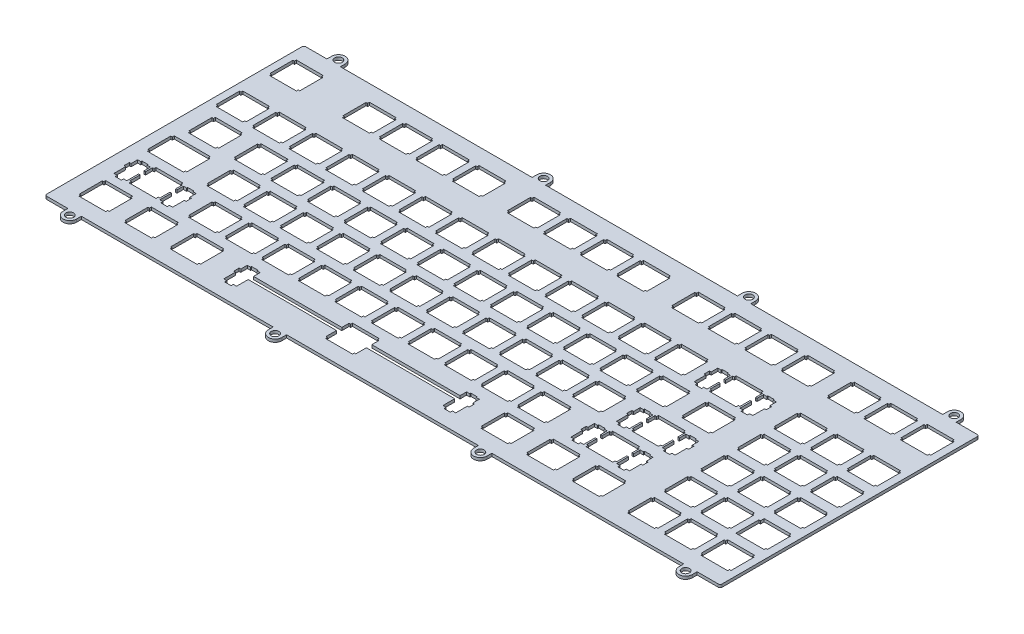
SolidWorks part; units mm, degrees
ref_plane "Front Plane" through (0, 0, 0) normal (0, 0, 1) x (1, 0, 0)
ref_plane "Top Plane" through (0, 0, 0) normal (0, 1, 0) x (1, 0, 0)
ref_plane "Right Plane" through (0, 0, 0) normal (1, 0, 0) x (0, 0, -1)
sketch "Sketch1" plane through (0, 0, 0) normal (0, 1, 0) x (1, 0, 0)
  line L0 (7.4991, 437.9187) -> (7.4632, 435.419)
  line L1 (0.4632, 435.419) -> (-11.5368, 435.419)
  line L2 (321.4632, 297.919) -> (321.4632, 300.419)
  line L3 (-11.5368, 435.419) -> (-11.5368, 300.419)
  line L4 (-7.7978, 425.9936) -> (-7.7978, 413.9844)
  line L5 (7.7978, 425.9936) -> (7.7978, 413.9844)
  line L6 (30.3022, 413.9844) -> (30.3022, 425.9936)
  line L7 (45.8978, 425.9936) -> (45.8978, 413.9844)
  line L8 (0.4991, 437.919) -> (0.4632, 435.419)
  line L9 (-11.5368, 300.419) -> (0.4632, 300.419)
  line L10 (7.4632, 300.419) -> (107.4632, 300.419)
  line L11 (107.4632, 435.419) -> (7.4632, 435.419)
  line L12 (243.0475, 341.884) -> (257.0175, 341.884)
  line L13 (257.0175, 341.884) -> (257.0175, 340.9036)
  line L14 (257.0175, 340.9036) -> (257.8303, 340.9036)
  line L15 (258.6431, 337.185) -> (258.6431, 340.5886)
  line L16 (258.6431, 340.5886) -> (260.3195, 340.5886)
  line L17 (260.3195, 340.5886) -> (260.3195, 341.122)
  line L18 (260.3195, 341.122) -> (263.6215, 341.122)
  line L19 (263.6215, 341.122) -> (263.6215, 340.5886)
  line L20 (263.6215, 340.5886) -> (265.2979, 340.5886)
  line L21 (265.2979, 340.5886) -> (265.2979, 337.185)
  line L22 (265.2979, 337.185) -> (266.1869, 337.185)
  line L23 (266.1869, 337.185) -> (266.1869, 334.391)
  line L24 (266.1869, 334.391) -> (265.2979, 334.391)
  line L25 (265.2979, 334.391) -> (265.2979, 328.295)
  line L26 (265.2979, 328.295) -> (263.6215, 328.295)
  line L27 (263.6215, 328.295) -> (263.6215, 327.152)
  line L28 (263.6215, 327.152) -> (260.3195, 327.152)
  line L29 (260.3195, 327.152) -> (260.3195, 328.295)
  line L30 (260.3195, 328.295) -> (258.6431, 328.295)
  line L31 (258.6431, 334.391) -> (258.6431, 328.295)
  line L32 (241.4219, 328.295) -> (241.4219, 334.391)
  line L33 (257.0175, 329.0824) -> (257.0175, 327.914)
  line L34 (257.0175, 327.914) -> (243.0475, 327.914)
  line L35 (243.0475, 327.914) -> (243.0475, 329.0824)
  line L36 (257.8303, 329.0824) -> (257.0175, 329.0824)
  line L37 (241.4219, 334.391) -> (242.2347, 334.391)
  line L38 (241.4219, 328.295) -> (239.7455, 328.295)
  line L39 (239.7455, 328.295) -> (239.7455, 327.152)
  line L40 (239.7455, 327.152) -> (236.4435, 327.152)
  line L41 (236.4435, 327.152) -> (236.4435, 328.295)
  line L42 (236.4435, 328.295) -> (234.7671, 328.295)
  line L43 (234.7671, 328.295) -> (234.7671, 334.391)
  line L44 (234.7671, 334.391) -> (233.8781, 334.391)
  line L45 (233.8781, 334.391) -> (233.8781, 337.185)
  line L46 (233.8781, 337.185) -> (234.7671, 337.185)
  line L47 (234.7671, 337.185) -> (234.7671, 340.5886)
  line L48 (234.7671, 340.5886) -> (236.4435, 340.5886)
  line L49 (236.4435, 340.5886) -> (236.4435, 341.122)
  line L50 (236.4435, 341.122) -> (239.7455, 341.122)
  line L51 (239.7455, 341.122) -> (239.7455, 340.5886)
  line L52 (239.7455, 340.5886) -> (241.4219, 340.5886)
  line L53 (242.2347, 334.391) -> (242.2347, 329.0824)
  line L54 (243.0475, 329.0824) -> (242.2347, 329.0824)
  line L55 (243.0475, 340.9036) -> (243.0475, 341.884)
  line L56 (250.19, 399.034) -> (264.16, 399.034)
  line L57 (264.16, 399.034) -> (264.16, 398.0536)
  line L58 (264.16, 398.0536) -> (264.9728, 398.0536)
  line L59 (265.7856, 394.335) -> (265.7856, 397.7386)
  line L60 (265.7856, 397.7386) -> (267.462, 397.7386)
  line L61 (267.462, 397.7386) -> (267.462, 398.272)
  line L62 (267.462, 398.272) -> (270.764, 398.272)
  line L63 (270.764, 398.272) -> (270.764, 397.7386)
  line L64 (270.764, 397.7386) -> (272.4404, 397.7386)
  line L65 (272.4404, 397.7386) -> (272.4404, 394.335)
  line L66 (272.4404, 394.335) -> (273.3294, 394.335)
  line L67 (273.3294, 394.335) -> (273.3294, 391.541)
  line L68 (273.3294, 391.541) -> (272.4404, 391.541)
  line L69 (272.4404, 391.541) -> (272.4404, 385.445)
  line L70 (272.4404, 385.445) -> (270.764, 385.445)
  line L71 (270.764, 385.445) -> (270.764, 384.302)
  line L72 (270.764, 384.302) -> (267.462, 384.302)
  line L73 (267.462, 384.302) -> (267.462, 385.445)
  line L74 (267.462, 385.445) -> (265.7856, 385.445)
  line L75 (265.7856, 391.541) -> (265.7856, 385.445)
  line L76 (248.5644, 385.445) -> (248.5644, 391.541)
  line L77 (264.16, 386.2324) -> (264.16, 385.064)
  line L78 (264.16, 385.064) -> (250.19, 385.064)
  line L79 (250.19, 385.064) -> (250.19, 386.2324)
  line L80 (264.9728, 386.2324) -> (264.16, 386.2324)
  line L81 (248.5644, 391.541) -> (249.3772, 391.541)
  line L82 (248.5644, 385.445) -> (246.888, 385.445)
  line L83 (246.888, 385.445) -> (246.888, 384.302)
  line L84 (246.888, 384.302) -> (243.586, 384.302)
  line L85 (243.586, 384.302) -> (243.586, 385.445)
  line L86 (243.586, 385.445) -> (241.9096, 385.445)
  line L87 (241.9096, 385.445) -> (241.9096, 391.541)
  line L88 (241.9096, 391.541) -> (241.0206, 391.541)
  line L89 (241.0206, 391.541) -> (241.0206, 394.335)
  line L90 (241.0206, 394.335) -> (241.9096, 394.335)
  line L91 (241.9096, 394.335) -> (241.9096, 397.7386)
  line L92 (241.9096, 397.7386) -> (243.586, 397.7386)
  line L93 (243.586, 397.7386) -> (243.586, 398.272)
  line L94 (243.586, 398.272) -> (246.888, 398.272)
  line L95 (246.888, 398.272) -> (246.888, 397.7386)
  line L96 (246.888, 397.7386) -> (248.5644, 397.7386)
  line L97 (249.3772, 391.541) -> (249.3772, 386.2324)
  line L98 (250.19, 386.2324) -> (249.3772, 386.2324)
  line L99 (250.19, 398.0536) -> (250.19, 399.034)
  line L100 (247.81, 360.934) -> (261.78, 360.934)
  line L101 (261.78, 360.934) -> (261.78, 359.9536)
  line L102 (261.78, 359.9536) -> (262.5928, 359.9536)
  line L103 (263.4056, 356.235) -> (263.4056, 359.6386)
  line L104 (263.4056, 359.6386) -> (265.082, 359.6386)
  line L105 (265.082, 359.6386) -> (265.082, 360.172)
  line L106 (265.082, 360.172) -> (268.384, 360.172)
  line L107 (268.384, 360.172) -> (268.384, 359.6386)
  line L108 (268.384, 359.6386) -> (270.0604, 359.6386)
  line L109 (270.0604, 359.6386) -> (270.0604, 356.235)
  line L110 (270.0604, 356.235) -> (270.9494, 356.235)
  line L111 (270.9494, 356.235) -> (270.9494, 353.441)
  line L112 (270.9494, 353.441) -> (270.0604, 353.441)
  line L113 (270.0604, 353.441) -> (270.0604, 347.345)
  line L114 (270.0604, 347.345) -> (268.384, 347.345)
  line L115 (268.384, 347.345) -> (268.384, 346.202)
  line L116 (268.384, 346.202) -> (265.082, 346.202)
  line L117 (265.082, 346.202) -> (265.082, 347.345)
  line L118 (265.082, 347.345) -> (263.4056, 347.345)
  line L119 (263.4056, 353.441) -> (263.4056, 347.345)
  line L120 (246.1844, 347.345) -> (246.1844, 353.441)
  line L121 (261.78, 348.1324) -> (261.78, 346.964)
  line L122 (261.78, 346.964) -> (247.81, 346.964)
  line L123 (247.81, 346.964) -> (247.81, 348.1324)
  line L124 (262.5928, 348.1324) -> (261.78, 348.1324)
  line L125 (246.1844, 353.441) -> (246.9972, 353.441)
  line L126 (246.1844, 347.345) -> (244.508, 347.345)
  line L127 (244.508, 347.345) -> (244.508, 346.202)
  line L128 (244.508, 346.202) -> (241.206, 346.202)
  line L129 (241.206, 346.202) -> (241.206, 347.345)
  line L130 (241.206, 347.345) -> (239.5296, 347.345)
  line L131 (239.5296, 347.345) -> (239.5296, 353.441)
  line L132 (239.5296, 353.441) -> (238.6406, 353.441)
  line L133 (238.6406, 353.441) -> (238.6406, 356.235)
  line L134 (238.6406, 356.235) -> (239.5296, 356.235)
  line L135 (239.5296, 356.235) -> (239.5296, 359.6386)
  line L136 (239.5296, 359.6386) -> (241.206, 359.6386)
  line L137 (241.206, 359.6386) -> (241.206, 360.172)
  line L138 (241.206, 360.172) -> (244.508, 360.172)
  line L139 (244.508, 360.172) -> (244.508, 359.6386)
  line L140 (244.508, 359.6386) -> (246.1844, 359.6386)
  line L141 (246.9972, 353.441) -> (246.9972, 348.1324)
  line L142 (247.81, 348.1324) -> (246.9972, 348.1324)
  line L143 (247.81, 359.9536) -> (247.81, 360.934)
  line L144 (4.9225, 341.884) -> (18.8925, 341.884)
  line L145 (18.8925, 341.884) -> (18.8925, 340.9036)
  line L146 (18.8925, 340.9036) -> (19.7053, 340.9036)
  line L147 (20.5181, 337.185) -> (20.5181, 340.5886)
  line L148 (20.5181, 340.5886) -> (22.1945, 340.5886)
  line L149 (22.1945, 340.5886) -> (22.1945, 341.122)
  line L150 (22.1945, 341.122) -> (25.4965, 341.122)
  line L151 (25.4965, 341.122) -> (25.4965, 340.5886)
  line L152 (25.4965, 340.5886) -> (27.1729, 340.5886)
  line L153 (27.1729, 340.5886) -> (27.1729, 337.185)
  line L154 (27.1729, 337.185) -> (28.0619, 337.185)
  line L155 (28.0619, 337.185) -> (28.0619, 334.391)
  line L156 (28.0619, 334.391) -> (27.1729, 334.391)
  line L157 (27.1729, 334.391) -> (27.1729, 328.295)
  line L158 (27.1729, 328.295) -> (25.4965, 328.295)
  line L159 (25.4965, 328.295) -> (25.4965, 327.152)
  line L160 (25.4965, 327.152) -> (22.1945, 327.152)
  line L161 (22.1945, 327.152) -> (22.1945, 328.295)
  line L162 (22.1945, 328.295) -> (20.5181, 328.295)
  line L163 (20.5181, 334.391) -> (20.5181, 328.295)
  line L164 (3.2969, 328.295) -> (3.2969, 334.391)
  line L165 (18.8925, 329.0824) -> (18.8925, 327.914)
  line L166 (18.8925, 327.914) -> (4.9225, 327.914)
  line L167 (4.9225, 327.914) -> (4.9225, 329.0824)
  line L168 (19.7053, 329.0824) -> (18.8925, 329.0824)
  line L169 (3.2969, 334.391) -> (4.1097, 334.391)
  line L170 (3.2969, 328.295) -> (1.6205, 328.295)
  line L171 (1.6205, 328.295) -> (1.6205, 327.152)
  line L172 (1.6205, 327.152) -> (-1.6815, 327.152)
  line L173 (-1.6815, 327.152) -> (-1.6815, 328.295)
  line L174 (-1.6815, 328.295) -> (-3.3579, 328.295)
  line L175 (-3.3579, 328.295) -> (-3.3579, 334.391)
  line L176 (-3.3579, 334.391) -> (-4.2469, 334.391)
  line L177 (-4.2469, 334.391) -> (-4.2469, 337.185)
  line L178 (-4.2469, 337.185) -> (-3.3579, 337.185)
  line L179 (-3.3579, 337.185) -> (-3.3579, 340.5886)
  line L180 (-3.3579, 340.5886) -> (-1.6815, 340.5886)
  line L181 (-1.6815, 340.5886) -> (-1.6815, 341.122)
  line L182 (-1.6815, 341.122) -> (1.6205, 341.122)
  line L183 (1.6205, 341.122) -> (1.6205, 340.5886)
  line L184 (1.6205, 340.5886) -> (3.2969, 340.5886)
  line L185 (4.1097, 334.391) -> (4.1097, 329.0824)
  line L186 (4.9225, 329.0824) -> (4.1097, 329.0824)
  line L187 (4.9225, 340.9036) -> (4.9225, 341.884)
  line L188 (126.3652, 322.834) -> (140.3352, 322.834)
  line L189 (140.3352, 322.834) -> (140.3352, 321.8536)
  line L190 (140.3352, 321.8536) -> (141.148, 321.8536)
  line L191 (125.5524, 321.8536) -> (125.5524, 318.135)
  line L192 (141.148, 309.8444) -> (141.148, 315.341)
  line L193 (79.5276, 318.135) -> (125.5524, 318.135)
  line L194 (141.148, 318.135) -> (187.1728, 318.135)
  line L195 (187.1728, 315.341) -> (141.148, 315.341)
  line L200 (79.5276, 315.341) -> (125.5524, 315.341)
  line L201 (187.1728, 318.135) -> (187.1728, 321.5386)
  line L202 (187.1728, 321.5386) -> (188.8492, 321.5386)
  line L203 (188.8492, 321.5386) -> (188.8492, 322.072)
  line L204 (188.8492, 322.072) -> (192.1512, 322.072)
  line L205 (192.1512, 322.072) -> (192.1512, 321.5386)
  line L206 (192.1512, 321.5386) -> (193.8276, 321.5386)
  line L207 (193.8276, 321.5386) -> (193.8276, 318.135)
  line L208 (193.8276, 318.135) -> (194.7166, 318.135)
  line L209 (194.7166, 318.135) -> (194.7166, 315.341)
  line L210 (194.7166, 315.341) -> (193.8276, 315.341)
  line L211 (193.8276, 315.341) -> (193.8276, 309.245)
  line L212 (193.8276, 309.245) -> (192.1512, 309.245)
  line L213 (192.1512, 309.245) -> (192.1512, 308.102)
  line L214 (192.1512, 308.102) -> (188.8492, 308.102)
  line L215 (188.8492, 308.102) -> (188.8492, 309.245)
  line L216 (188.8492, 309.245) -> (187.1728, 309.245)
  line L228 (141.148, 309.8444) -> (140.3352, 309.8444)
  line L229 (140.3352, 309.8444) -> (140.3352, 308.864)
  line L230 (140.3352, 308.864) -> (126.3652, 308.864)
  line L231 (126.3652, 308.864) -> (126.3652, 309.8444)
  line L232 (126.3652, 309.8444) -> (125.5524, 309.8444)
  line L241 (141.148, 318.135) -> (141.148, 321.8536)
  line L242 (79.5276, 315.341) -> (79.5276, 309.245)
  line L244 (79.5276, 309.245) -> (77.8512, 309.245)
  line L245 (77.8512, 309.245) -> (77.8512, 308.102)
  line L246 (77.8512, 308.102) -> (74.5492, 308.102)
  line L247 (74.5492, 308.102) -> (74.5492, 309.245)
  line L248 (74.5492, 309.245) -> (72.8728, 309.245)
  line L249 (72.8728, 309.245) -> (72.8728, 315.341)
  line L250 (72.8728, 315.341) -> (71.9838, 315.341)
  line L251 (71.9838, 315.341) -> (71.9838, 318.135)
  line L252 (71.9838, 318.135) -> (72.8728, 318.135)
  line L253 (72.8728, 318.135) -> (72.8728, 321.5386)
  line L254 (72.8728, 321.5386) -> (74.5492, 321.5386)
  line L255 (74.5492, 321.5386) -> (74.5492, 322.072)
  line L256 (74.5492, 322.072) -> (77.8512, 322.072)
  line L257 (77.8512, 322.072) -> (77.8512, 321.5386)
  line L258 (77.8512, 321.5386) -> (79.5276, 321.5386)
  line L259 (79.5276, 321.5386) -> (79.5276, 318.135)
  line L260 (125.5524, 315.341) -> (125.5524, 309.8444)
  line L270 (125.5524, 321.8536) -> (126.3652, 321.8536)
  line L271 (126.3652, 321.8536) -> (126.3652, 322.834)
  line L272 (-4.602, 360.934) -> (14.131, 360.934)
  line L273 (14.131, 360.934) -> (14.131, 359.9536)
  line L274 (14.131, 359.9536) -> (14.9438, 359.9536)
  line L275 (-5.4148, 359.9536) -> (-5.4148, 347.9444)
  line L276 (14.9438, 347.9444) -> (14.9438, 359.9536)
  line L277 (336.7278, 359.9536) -> (336.7278, 347.9444)
  line L278 (321.1322, 347.9444) -> (321.1322, 359.9536)
  line L279 (317.6778, 359.9536) -> (317.6778, 347.9444)
  line L280 (14.9438, 347.9444) -> (14.131, 347.9444)
  line L281 (14.131, 347.9444) -> (14.131, 346.964)
  line L282 (14.131, 346.964) -> (-4.602, 346.964)
  line L283 (-4.602, 346.964) -> (-4.602, 347.9444)
  line L284 (-4.602, 347.9444) -> (-5.4148, 347.9444)
  line L285 (302.0822, 347.9444) -> (302.0822, 359.9536)
  line L286 (298.6278, 359.9536) -> (298.6278, 347.9444)
  line L287 (49.3522, 425.9936) -> (49.3522, 413.9844)
  line L288 (64.9478, 425.9936) -> (64.9478, 413.9844)
  line L289 (283.0322, 347.9444) -> (283.0322, 359.9536)
  line L290 (-5.4148, 359.9536) -> (-4.602, 359.9536)
  line L291 (-4.602, 359.9536) -> (-4.602, 360.934)
  line L295 (68.4022, 413.9844) -> (68.4022, 425.9936)
  line L296 (83.9978, 425.9936) -> (83.9978, 413.9844)
  line L297 (87.4522, 413.9844) -> (87.4522, 425.9936)
  line L298 (103.0478, 425.9936) -> (103.0478, 413.9844)
  line L299 (116.0272, 413.984) -> (116.0272, 425.9931)
  line L305 (131.6228, 425.9931) -> (131.6228, 413.984)
  line L306 (135.0772, 413.9844) -> (135.0772, 425.9936)
  line L307 (150.6728, 425.9936) -> (150.6728, 413.9844)
  line L308 (154.1272, 413.9844) -> (154.1272, 425.9936)
  line L309 (169.7228, 425.9936) -> (169.7228, 413.9844)
  line L312 (254.9524, 322.834) -> (268.9224, 322.834)
  line L313 (268.9224, 322.834) -> (268.9224, 321.8536)
  line L314 (268.9224, 321.8536) -> (269.7352, 321.8536)
  line L315 (173.1728, 425.9936) -> (173.1728, 413.9844)
  line L316 (188.7684, 413.9844) -> (188.7684, 425.9936)
  line L317 (201.7522, 425.9936) -> (201.7522, 413.9844)
  line L318 (217.3478, 413.9844) -> (217.3478, 425.9936)
  line L319 (258.9022, 425.9936) -> (258.9022, 413.9844)
  line L320 (269.7352, 309.8444) -> (268.9224, 309.8444)
  line L321 (268.9224, 309.8444) -> (268.9224, 308.864)
  line L322 (268.9224, 308.864) -> (254.9524, 308.864)
  line L323 (254.9524, 308.864) -> (254.9524, 309.8444)
  line L324 (254.9524, 309.8444) -> (254.1396, 309.8444)
  line L325 (255.4478, 413.9844) -> (255.4478, 425.9936)
  line L326 (239.8522, 425.9936) -> (239.8522, 413.9844)
  line L327 (236.3978, 413.9844) -> (236.3978, 425.9936)
  line L328 (220.8022, 425.9936) -> (220.8022, 413.9844)
  line L329 (274.4978, 413.9844) -> (274.4978, 425.9936)
  line L330 (254.1396, 321.8536) -> (254.9524, 321.8536)
  line L331 (254.9524, 321.8536) -> (254.9524, 322.834)
  line L332 (231.1398, 322.834) -> (245.1098, 322.834)
  line L333 (245.1098, 322.834) -> (245.1098, 321.8536)
  line L334 (245.1098, 321.8536) -> (245.9226, 321.8536)
  line L335 (283.0322, 425.9936) -> (283.0322, 413.9844)
  line L336 (107.4632, 437.919) -> (107.4632, 435.419)
  line L337 (298.6278, 413.9844) -> (298.6278, 425.9936)
  line L338 (302.0822, 425.9936) -> (302.0822, 413.9844)
  line L339 (317.6778, 413.9844) -> (317.6778, 425.9936)
  line L340 (245.9226, 309.8444) -> (245.1098, 309.8444)
  line L341 (245.1098, 309.8444) -> (245.1098, 308.864)
  line L342 (245.1098, 308.864) -> (231.1398, 308.864)
  line L343 (231.1398, 308.864) -> (231.1398, 309.8444)
  line L344 (231.1398, 309.8444) -> (230.327, 309.8444)
  line L345 (321.1322, 425.9936) -> (321.1322, 413.9844)
  line L346 (336.7278, 413.9844) -> (336.7278, 425.9936)
  line L347 (-7.7978, 398.0536) -> (-7.7978, 386.0444)
  line L348 (7.7978, 386.0444) -> (7.7978, 398.0536)
  line L349 (11.2522, 398.0536) -> (11.2522, 386.0444)
  line L350 (230.327, 321.8536) -> (231.1398, 321.8536)
  line L351 (231.1398, 321.8536) -> (231.1398, 322.834)
  line L352 (207.3272, 322.834) -> (221.2972, 322.834)
  line L353 (221.2972, 322.834) -> (221.2972, 321.8536)
  line L354 (221.2972, 321.8536) -> (222.11, 321.8536)
  line L355 (26.8478, 386.0444) -> (26.8478, 398.0536)
  line L356 (30.3022, 398.0536) -> (30.3022, 386.0444)
  line L357 (45.8978, 386.0444) -> (45.8978, 398.0536)
  line L358 (49.3522, 398.0536) -> (49.3522, 386.0444)
  line L359 (64.9478, 386.0444) -> (64.9478, 398.0536)
  line L360 (222.11, 309.8444) -> (221.2972, 309.8444)
  line L361 (221.2972, 309.8444) -> (221.2972, 308.864)
  line L362 (221.2972, 308.864) -> (207.3272, 308.864)
  line L363 (207.3272, 308.864) -> (207.3272, 309.8444)
  line L364 (207.3272, 309.8444) -> (206.5144, 309.8444)
  line L365 (68.4022, 398.0536) -> (68.4022, 386.0444)
  line L366 (83.9978, 386.0444) -> (83.9978, 398.0536)
  line L367 (87.4522, 398.0536) -> (87.4522, 386.0444)
  line L368 (103.0478, 386.0444) -> (103.0478, 398.0536)
  line L369 (106.5022, 398.0536) -> (106.5022, 386.0444)
  line L370 (206.5144, 321.8536) -> (207.3272, 321.8536)
  line L371 (207.3272, 321.8536) -> (207.3272, 322.834)
  line L372 (45.4032, 322.834) -> (59.3732, 322.834)
  line L373 (59.3732, 322.834) -> (59.3732, 321.8536)
  line L374 (59.3732, 321.8536) -> (60.186, 321.8536)
  line L375 (122.0978, 386.0444) -> (122.0978, 398.0536)
  line L376 (125.5522, 398.0536) -> (125.5522, 386.0444)
  line L377 (141.1478, 386.0444) -> (141.1478, 398.0536)
  line L378 (144.6022, 398.0536) -> (144.6022, 386.0444)
  line L379 (160.1978, 386.0444) -> (160.1978, 398.0536)
  line L380 (60.186, 309.8444) -> (59.3732, 309.8444)
  line L381 (59.3732, 309.8444) -> (59.3732, 308.864)
  line L382 (59.3732, 308.864) -> (45.4032, 308.864)
  line L383 (45.4032, 308.864) -> (45.4032, 309.8444)
  line L384 (45.4032, 309.8444) -> (44.5904, 309.8444)
  line L385 (163.6522, 398.0536) -> (163.6522, 386.0444)
  line L386 (179.2478, 386.0444) -> (179.2478, 398.0536)
  line L387 (182.7022, 398.0536) -> (182.7022, 386.0444)
  line L388 (198.2978, 386.0444) -> (198.2978, 398.0536)
  line L389 (201.7522, 398.0536) -> (201.7522, 386.0444)
  line L390 (44.5904, 321.8536) -> (45.4032, 321.8536)
  line L391 (45.4032, 321.8536) -> (45.4032, 322.834)
  line L392 (21.5906, 322.834) -> (35.5606, 322.834)
  line L393 (35.5606, 322.834) -> (35.5606, 321.8536)
  line L394 (35.5606, 321.8536) -> (36.3734, 321.8536)
  line L395 (217.3478, 386.0444) -> (217.3478, 398.0536)
  line L396 (220.8022, 398.0536) -> (220.8022, 386.0444)
  line L397 (236.3978, 386.0444) -> (236.3978, 398.0536)
  line L398 (283.0322, 398.0536) -> (283.0322, 386.0444)
  line L399 (298.6278, 386.0444) -> (298.6278, 398.0536)
  line L400 (36.3734, 309.8444) -> (35.5606, 309.8444)
  line L401 (35.5606, 309.8444) -> (35.5606, 308.864)
  line L402 (35.5606, 308.864) -> (21.5906, 308.864)
  line L403 (21.5906, 308.864) -> (21.5906, 309.8444)
  line L404 (21.5906, 309.8444) -> (20.7778, 309.8444)
  line L405 (302.0822, 398.0536) -> (302.0822, 386.0444)
  line L406 (317.6778, 386.0444) -> (317.6778, 398.0536)
  line L407 (321.1322, 398.0536) -> (321.1322, 386.0444)
  line L408 (336.7278, 386.0444) -> (336.7278, 398.0536)
  line L409 (336.7278, 379.0036) -> (336.7278, 366.9944)
  line L410 (20.7778, 321.8536) -> (21.5906, 321.8536)
  line L411 (21.5906, 321.8536) -> (21.5906, 322.834)
  line L412 (-2.222, 322.834) -> (11.748, 322.834)
  line L413 (11.748, 322.834) -> (11.748, 321.8536)
  line L414 (11.748, 321.8536) -> (12.5608, 321.8536)
  line L415 (321.1322, 366.9944) -> (321.1322, 379.0036)
  line L416 (317.6778, 379.0036) -> (317.6778, 366.9944)
  line L417 (302.0822, 366.9944) -> (302.0822, 379.0036)
  line L418 (298.6278, 379.0036) -> (298.6278, 366.9944)
  line L419 (283.0322, 366.9944) -> (283.0322, 379.0036)
  line L420 (12.5608, 309.8444) -> (11.748, 309.8444)
  line L421 (11.748, 309.8444) -> (11.748, 308.864)
  line L422 (11.748, 308.864) -> (-2.222, 308.864)
  line L423 (-2.222, 308.864) -> (-2.222, 309.8444)
  line L424 (-2.222, 309.8444) -> (-3.0348, 309.8444)
  line L425 (321.945, 360.934) -> (335.915, 360.934)
  line L426 (335.915, 360.934) -> (335.915, 359.9536)
  line L427 (114.4632, 437.919) -> (114.4632, 435.419)
  line L428 (114.4632, 435.419) -> (214.4632, 435.419)
  line L429 (214.4632, 437.919) -> (214.4632, 435.419)
  line L430 (-3.0348, 321.8536) -> (-2.222, 321.8536)
  line L431 (-2.222, 321.8536) -> (-2.222, 322.834)
  line L432 (35.8775, 341.884) -> (49.8475, 341.884)
  line L433 (49.8475, 341.884) -> (49.8475, 340.9036)
  line L434 (49.8475, 340.9036) -> (50.6603, 340.9036)
  line L436 (221.4632, 437.919) -> (221.4632, 435.419)
  line L438 (302.0794, 340.9036) -> (302.0794, 328.8944)
  line L439 (317.675, 328.8944) -> (317.675, 340.9036)
  line L440 (50.6603, 328.8944) -> (49.8475, 328.8944)
  line L441 (49.8475, 328.8944) -> (49.8475, 327.914)
  line L442 (49.8475, 327.914) -> (35.8775, 327.914)
  line L443 (35.8775, 327.914) -> (35.8775, 328.8944)
  line L444 (35.8775, 328.8944) -> (35.0647, 328.8944)
  line L445 (221.4632, 435.419) -> (321.4632, 435.419)
  line L446 (0.4632, 297.919) -> (0.4632, 300.419)
  line L447 (283.0322, 321.8536) -> (283.0322, 309.8444)
  line L448 (298.6278, 309.8444) -> (298.6278, 321.8536)
  line L449 (302.0822, 321.8536) -> (302.0822, 309.8444)
  line L450 (35.0647, 340.9036) -> (35.8775, 340.9036)
  line L451 (35.8775, 340.9036) -> (35.8775, 341.884)
  line L452 (321.945, 322.834) -> (335.915, 322.834)
  line L453 (335.915, 322.834) -> (335.915, 321.8536)
  line L454 (335.915, 321.8536) -> (336.7278, 321.8536)
  line L455 (317.6778, 309.8444) -> (317.6778, 321.8536)
  line L456 (321.1322, 321.8536) -> (321.1322, 309.8444)
  line L457 (336.7278, 309.8444) -> (336.7278, 321.8536)
  line L458 (-3.0353, 379.0036) -> (-3.0353, 366.9944)
  line L459 (12.5603, 366.9944) -> (12.5603, 379.0036)
  line L460 (336.7278, 309.8444) -> (335.915, 309.8444)
  line L461 (335.915, 309.8444) -> (335.915, 308.864)
  line L462 (335.915, 308.864) -> (321.945, 308.864)
  line L463 (321.945, 308.864) -> (321.945, 309.8444)
  line L464 (321.945, 309.8444) -> (321.1322, 309.8444)
  line L465 (20.7772, 379.0036) -> (20.7772, 366.9944)
  line L466 (36.3728, 366.9944) -> (36.3728, 379.0036)
  line L467 (39.8272, 379.0036) -> (39.8272, 366.9944)
  line L468 (55.4228, 366.9944) -> (55.4228, 379.0036)
  line L469 (58.8772, 379.0036) -> (58.8772, 366.9944)
  line L470 (321.1322, 321.8536) -> (321.945, 321.8536)
  line L471 (321.945, 321.8536) -> (321.945, 322.834)
  line L472 (302.895, 322.834) -> (316.865, 322.834)
  line L473 (316.865, 322.834) -> (316.865, 321.8536)
  line L474 (316.865, 321.8536) -> (317.6778, 321.8536)
  line L475 (74.4728, 366.9944) -> (74.4728, 379.0036)
  line L476 (77.9272, 379.0036) -> (77.9272, 366.9944)
  line L477 (93.5228, 366.9944) -> (93.5228, 379.0036)
  line L478 (96.9772, 366.9944) -> (96.9772, 379.0036)
  line L479 (112.5728, 379.0036) -> (112.5728, 366.9944)
  line L480 (317.6778, 309.8444) -> (316.865, 309.8444)
  line L481 (316.865, 309.8444) -> (316.865, 308.864)
  line L482 (316.865, 308.864) -> (302.895, 308.864)
  line L483 (302.895, 308.864) -> (302.895, 309.8444)
  line L484 (302.895, 309.8444) -> (302.0822, 309.8444)
  line L485 (116.0272, 366.9944) -> (116.0272, 379.0036)
  line L486 (131.6228, 379.0036) -> (131.6228, 366.9944)
  line L487 (135.0772, 366.9944) -> (135.0772, 379.0036)
  line L488 (150.6728, 379.0036) -> (150.6728, 366.9944)
  line L489 (154.1272, 366.9944) -> (154.1272, 379.0036)
  line L490 (302.0822, 321.8536) -> (302.895, 321.8536)
  line L491 (302.895, 321.8536) -> (302.895, 322.834)
  line L492 (283.845, 322.834) -> (297.815, 322.834)
  line L493 (297.815, 322.834) -> (297.815, 321.8536)
  line L494 (297.815, 321.8536) -> (298.6278, 321.8536)
  line L495 (169.7228, 379.0036) -> (169.7228, 366.9944)
  line L496 (173.1772, 379.0036) -> (173.1772, 366.9944)
  line L497 (188.7728, 379.0036) -> (188.7728, 366.9944)
  line L498 (192.2272, 366.9944) -> (192.2272, 379.0036)
  line L499 (207.8228, 379.0036) -> (207.8228, 366.9944)
  line L500 (298.6278, 309.8444) -> (297.815, 309.8444)
  line L501 (297.815, 309.8444) -> (297.815, 308.864)
  line L502 (297.815, 308.864) -> (283.845, 308.864)
  line L503 (283.845, 308.864) -> (283.845, 309.8444)
  line L504 (283.845, 309.8444) -> (283.0322, 309.8444)
  line L505 (211.2772, 366.9944) -> (211.2772, 379.0036)
  line L506 (226.8728, 379.0036) -> (226.8728, 366.9944)
  line L507 (230.3272, 366.9944) -> (230.3272, 379.0036)
  line L508 (245.9228, 379.0036) -> (245.9228, 366.9944)
  line L509 (254.1397, 366.9944) -> (254.1397, 379.0036)
  line L510 (283.0322, 321.8536) -> (283.845, 321.8536)
  line L511 (283.845, 321.8536) -> (283.845, 322.834)
  line L512 (302.8922, 341.884) -> (316.8622, 341.884)
  line L513 (316.8622, 341.884) -> (316.8622, 340.9036)
  line L514 (316.8622, 340.9036) -> (317.675, 340.9036)
  line L515 (269.7353, 379.0036) -> (269.7353, 366.9944)
  line L516 (25.5397, 359.9536) -> (25.5397, 347.9444)
  line L517 (41.1353, 347.9444) -> (41.1353, 359.9536)
  line L518 (44.5897, 359.9536) -> (44.5897, 347.9444)
  line L519 (60.1853, 347.9444) -> (60.1853, 359.9536)
  line L520 (317.675, 328.8944) -> (316.8622, 328.8944)
  line L521 (316.8622, 328.8944) -> (316.8622, 327.914)
  line L522 (316.8622, 327.914) -> (302.8922, 327.914)
  line L523 (302.8922, 327.914) -> (302.8922, 328.8944)
  line L524 (302.8922, 328.8944) -> (302.0794, 328.8944)
  line L525 (63.6397, 359.9536) -> (63.6397, 347.9444)
  line L526 (79.2353, 347.9444) -> (79.2353, 359.9536)
  line L527 (82.6897, 359.9536) -> (82.6897, 347.9444)
  line L528 (98.2853, 347.9444) -> (98.2853, 359.9536)
  line L529 (101.7397, 359.9536) -> (101.7397, 347.9444)
  line L530 (302.0794, 340.9036) -> (302.8922, 340.9036)
  line L531 (302.8922, 340.9036) -> (302.8922, 341.884)
  line L532 (207.3275, 341.884) -> (221.2975, 341.884)
  line L533 (221.2975, 341.884) -> (221.2975, 340.9036)
  line L534 (221.2975, 340.9036) -> (222.1103, 340.9036)
  line L535 (117.3353, 347.9444) -> (117.3353, 359.9536)
  line L536 (120.7897, 359.9536) -> (120.7897, 347.9444)
  line L537 (136.3853, 347.9444) -> (136.3853, 359.9536)
  line L538 (139.8397, 359.9536) -> (139.8397, 347.9444)
  line L539 (155.4353, 347.9444) -> (155.4353, 359.9536)
  line L540 (222.1103, 328.8944) -> (221.2975, 328.8944)
  line L541 (221.2975, 328.8944) -> (221.2975, 327.914)
  line L542 (221.2975, 327.914) -> (207.3275, 327.914)
  line L543 (207.3275, 327.914) -> (207.3275, 328.8944)
  line L544 (207.3275, 328.8944) -> (206.5147, 328.8944)
  line L545 (158.8897, 359.9536) -> (158.8897, 347.9444)
  line L546 (174.4853, 347.9444) -> (174.4853, 359.9536)
  line L547 (177.9397, 359.9536) -> (177.9397, 347.9444)
  line L548 (193.5353, 347.9444) -> (193.5353, 359.9536)
  line L549 (196.9897, 347.9444) -> (196.9897, 359.9536)
  line L550 (206.5147, 340.9036) -> (207.3275, 340.9036)
  line L551 (207.3275, 340.9036) -> (207.3275, 341.884)
  line L552 (188.2775, 341.884) -> (202.2475, 341.884)
  line L553 (202.2475, 341.884) -> (202.2475, 340.9036)
  line L554 (202.2475, 340.9036) -> (203.0603, 340.9036)
  line L555 (212.5853, 347.9444) -> (212.5853, 359.9536)
  line L556 (216.0397, 347.9444) -> (216.0397, 359.9536)
  line L557 (231.6353, 359.9536) -> (231.6353, 347.9444)
  line L558 (35.0647, 340.9036) -> (35.0647, 328.8944)
  line L559 (50.6603, 328.8944) -> (50.6603, 340.9036)
  line L560 (203.0603, 328.8944) -> (202.2475, 328.8944)
  line L561 (202.2475, 328.8944) -> (202.2475, 327.914)
  line L562 (202.2475, 327.914) -> (188.2775, 327.914)
  line L563 (188.2775, 327.914) -> (188.2775, 328.8944)
  line L564 (188.2775, 328.8944) -> (187.4647, 328.8944)
  line L565 (54.1147, 340.9036) -> (54.1147, 328.8944)
  line L566 (69.7103, 328.8944) -> (69.7103, 340.9036)
  line L567 (73.1647, 340.9036) -> (73.1647, 328.8944)
  line L568 (88.7603, 328.8944) -> (88.7603, 340.9036)
  line L569 (92.2147, 340.9036) -> (92.2147, 328.8944)
  line L570 (187.4647, 340.9036) -> (188.2775, 340.9036)
  line L571 (188.2775, 340.9036) -> (188.2775, 341.884)
  line L572 (169.2275, 341.884) -> (183.1975, 341.884)
  line L573 (183.1975, 341.884) -> (183.1975, 340.9036)
  line L574 (183.1975, 340.9036) -> (184.0103, 340.9036)
  line L575 (107.8103, 328.8944) -> (107.8103, 340.9036)
  line L576 (111.2647, 340.9036) -> (111.2647, 328.8944)
  line L577 (126.8603, 328.8944) -> (126.8603, 340.9036)
  line L578 (-3.0348, 321.8536) -> (-3.0348, 309.8444)
  line L579 (12.5608, 309.8444) -> (12.5608, 321.8536)
  line L580 (184.0103, 328.8944) -> (183.1975, 328.8944)
  line L581 (183.1975, 328.8944) -> (183.1975, 327.914)
  line L582 (183.1975, 327.914) -> (169.2275, 327.914)
  line L583 (169.2275, 327.914) -> (169.2275, 328.8944)
  line L584 (169.2275, 328.8944) -> (168.4147, 328.8944)
  line L585 (20.7778, 321.8536) -> (20.7778, 309.8444)
  line L586 (36.3734, 309.8444) -> (36.3734, 321.8536)
  line L587 (44.5904, 321.8536) -> (44.5904, 309.8444)
  line L588 (60.186, 309.8444) -> (60.186, 321.8536)
  line L589 (130.3147, 340.9036) -> (130.3147, 328.8944)
  line L590 (168.4147, 340.9036) -> (169.2275, 340.9036)
  line L591 (169.2275, 340.9036) -> (169.2275, 341.884)
  line L592 (150.1775, 341.884) -> (164.1475, 341.884)
  line L593 (164.1475, 341.884) -> (164.1475, 340.9036)
  line L594 (164.1475, 340.9036) -> (164.9603, 340.9036)
  line L595 (145.9103, 328.8944) -> (145.9103, 340.9036)
  line L596 (149.3647, 340.9036) -> (149.3647, 328.8944)
  line L597 (164.9603, 328.8944) -> (164.9603, 340.9036)
  line L598 (168.4147, 340.9036) -> (168.4147, 328.8944)
  line L599 (184.0103, 328.8944) -> (184.0103, 340.9036)
  line L600 (164.9603, 328.8944) -> (164.1475, 328.8944)
  line L601 (164.1475, 328.8944) -> (164.1475, 327.914)
  line L602 (164.1475, 327.914) -> (150.1775, 327.914)
  line L603 (150.1775, 327.914) -> (150.1775, 328.8944)
  line L604 (150.1775, 328.8944) -> (149.3647, 328.8944)
  line L605 (187.4647, 340.9036) -> (187.4647, 328.8944)
  line L606 (203.0603, 328.8944) -> (203.0603, 340.9036)
  line L607 (206.5147, 340.9036) -> (206.5147, 328.8944)
  line L608 (222.1103, 328.8944) -> (222.1103, 340.9036)
  line L610 (149.3647, 340.9036) -> (150.1775, 340.9036)
  line L611 (150.1775, 340.9036) -> (150.1775, 341.884)
  line L612 (131.1275, 341.884) -> (145.0975, 341.884)
  line L613 (145.0975, 341.884) -> (145.0975, 340.9036)
  line L614 (145.0975, 340.9036) -> (145.9103, 340.9036)
  line L616 (206.5144, 321.8536) -> (206.5144, 309.8444)
  line L617 (222.11, 309.8444) -> (222.11, 321.8536)
  line L618 (230.327, 321.8536) -> (230.327, 309.8444)
  line L619 (245.9226, 309.8444) -> (245.9226, 321.8536)
  line L620 (145.9103, 328.8944) -> (145.0975, 328.8944)
  line L621 (145.0975, 328.8944) -> (145.0975, 327.914)
  line L622 (145.0975, 327.914) -> (131.1275, 327.914)
  line L623 (131.1275, 327.914) -> (131.1275, 328.8944)
  line L624 (131.1275, 328.8944) -> (130.3147, 328.8944)
  line L625 (7.4632, 297.919) -> (7.4632, 300.419)
  line L626 (254.1396, 321.8536) -> (254.1396, 309.8444)
  line L627 (269.7352, 309.8444) -> (269.7352, 321.8536)
  line L628 (187.1728, 309.245) -> (187.1728, 315.341)
  line L630 (130.3147, 340.9036) -> (131.1275, 340.9036)
  line L631 (131.1275, 340.9036) -> (131.1275, 341.884)
  line L632 (112.0775, 341.884) -> (126.0475, 341.884)
  line L633 (126.0475, 341.884) -> (126.0475, 340.9036)
  line L634 (126.0475, 340.9036) -> (126.8603, 340.9036)
  line L640 (126.8603, 328.8944) -> (126.0475, 328.8944)
  line L641 (126.0475, 328.8944) -> (126.0475, 327.914)
  line L642 (126.0475, 327.914) -> (112.0775, 327.914)
  line L643 (112.0775, 327.914) -> (112.0775, 328.8944)
  line L644 (112.0775, 328.8944) -> (111.2647, 328.8944)
  line L646 (3.2969, 340.5886) -> (3.2969, 337.185)
  line L647 (4.1097, 340.9036) -> (4.9225, 340.9036)
  line L648 (3.2969, 337.185) -> (4.1097, 337.185)
  line L649 (4.1097, 337.185) -> (4.1097, 340.9036)
  line L650 (111.2647, 340.9036) -> (112.0775, 340.9036)
  line L651 (112.0775, 340.9036) -> (112.0775, 341.884)
  line L652 (93.0275, 341.884) -> (106.9975, 341.884)
  line L653 (106.9975, 341.884) -> (106.9975, 340.9036)
  line L654 (106.9975, 340.9036) -> (107.8103, 340.9036)
  line L655 (19.7053, 329.0824) -> (19.7053, 334.391)
  line L656 (246.1844, 359.6386) -> (246.1844, 356.235)
  line L657 (20.5181, 334.391) -> (19.7053, 334.391)
  line L658 (19.7053, 340.9036) -> (19.7053, 337.185)
  line L659 (19.7053, 337.185) -> (20.5181, 337.185)
  line L660 (107.8103, 328.8944) -> (106.9975, 328.8944)
  line L661 (106.9975, 328.8944) -> (106.9975, 327.914)
  line L662 (106.9975, 327.914) -> (93.0275, 327.914)
  line L663 (93.0275, 327.914) -> (93.0275, 328.8944)
  line L664 (93.0275, 328.8944) -> (92.2147, 328.8944)
  line L665 (246.9972, 359.9536) -> (247.81, 359.9536)
  line L666 (246.1844, 356.235) -> (246.9972, 356.235)
  line L667 (246.9972, 356.235) -> (246.9972, 359.9536)
  line L668 (262.5928, 348.1324) -> (262.5928, 353.441)
  line L669 (263.4056, 353.441) -> (262.5928, 353.441)
  line L670 (92.2147, 340.9036) -> (93.0275, 340.9036)
  line L671 (93.0275, 340.9036) -> (93.0275, 341.884)
  line L672 (73.9775, 341.884) -> (87.9475, 341.884)
  line L673 (87.9475, 341.884) -> (87.9475, 340.9036)
  line L674 (87.9475, 340.9036) -> (88.7603, 340.9036)
  line L675 (262.5928, 359.9536) -> (262.5928, 356.235)
  line L676 (262.5928, 356.235) -> (263.4056, 356.235)
  line L677 (241.4219, 340.5886) -> (241.4219, 337.185)
  line L678 (242.2347, 340.9036) -> (243.0475, 340.9036)
  line L679 (241.4219, 337.185) -> (242.2347, 337.185)
  line L680 (88.7603, 328.8944) -> (87.9475, 328.8944)
  line L681 (87.9475, 328.8944) -> (87.9475, 327.914)
  line L682 (87.9475, 327.914) -> (73.9775, 327.914)
  line L683 (73.9775, 327.914) -> (73.9775, 328.8944)
  line L684 (73.9775, 328.8944) -> (73.1647, 328.8944)
  line L685 (242.2347, 337.185) -> (242.2347, 340.9036)
  line L686 (257.8303, 329.0824) -> (257.8303, 334.391)
  line L687 (258.6431, 334.391) -> (257.8303, 334.391)
  line L688 (257.8303, 340.9036) -> (257.8303, 337.185)
  line L689 (257.8303, 337.185) -> (258.6431, 337.185)
  line L690 (73.1647, 340.9036) -> (73.9775, 340.9036)
  line L691 (73.9775, 340.9036) -> (73.9775, 341.884)
  line L692 (54.9275, 341.884) -> (68.8975, 341.884)
  line L693 (68.8975, 341.884) -> (68.8975, 340.9036)
  line L694 (68.8975, 340.9036) -> (69.7103, 340.9036)
  line L695 (248.5644, 397.7386) -> (248.5644, 394.335)
  line L696 (249.3772, 398.0536) -> (250.19, 398.0536)
  line L697 (248.5644, 394.335) -> (249.3772, 394.335)
  line L698 (249.3772, 394.335) -> (249.3772, 398.0536)
  line L699 (264.9728, 386.2324) -> (264.9728, 391.541)
  line L700 (69.7103, 328.8944) -> (68.8975, 328.8944)
  line L701 (68.8975, 328.8944) -> (68.8975, 327.914)
  line L702 (68.8975, 327.914) -> (54.9275, 327.914)
  line L703 (54.9275, 327.914) -> (54.9275, 328.8944)
  line L704 (54.9275, 328.8944) -> (54.1147, 328.8944)
  line L705 (265.7856, 391.541) -> (264.9728, 391.541)
  line L706 (264.9728, 398.0536) -> (264.9728, 394.335)
  line L707 (264.9728, 394.335) -> (265.7856, 394.335)
  line L710 (54.1147, 340.9036) -> (54.9275, 340.9036)
  line L711 (54.9275, 340.9036) -> (54.9275, 341.884)
  line L712 (216.8525, 360.934) -> (230.8225, 360.934)
  line L713 (230.8225, 360.934) -> (230.8225, 359.9536)
  line L714 (230.8225, 359.9536) -> (231.6353, 359.9536)
  line L715 (107.4632, 297.919) -> (107.4632, 300.419)
  line L716 (114.4632, 297.919) -> (114.4632, 300.419)
  line L717 (328.4632, 297.919) -> (328.4632, 300.419)
  line L718 (328.4632, 300.419) -> (340.4632, 300.419)
  line L719 (340.4632, 300.419) -> (340.4632, 435.419)
  line L720 (231.6353, 347.9444) -> (230.8225, 347.9444)
  line L721 (230.8225, 347.9444) -> (230.8225, 346.964)
  line L722 (230.8225, 346.964) -> (216.8525, 346.964)
  line L723 (216.8525, 346.964) -> (216.8525, 347.9444)
  line L724 (216.8525, 347.9444) -> (216.0397, 347.9444)
  line L727 (321.4632, 300.419) -> (221.4632, 300.419)
  line L728 (214.4632, 297.919) -> (214.4632, 300.419)
  line L729 (221.4632, 297.919) -> (221.4632, 300.419)
  line L730 (216.0397, 359.9536) -> (216.8525, 359.9536)
  line L731 (216.8525, 359.9536) -> (216.8525, 360.934)
  line L732 (197.8025, 360.934) -> (211.7725, 360.934)
  line L733 (211.7725, 360.934) -> (211.7725, 359.9536)
  line L734 (211.7725, 359.9536) -> (212.5853, 359.9536)
  line L735 (214.4632, 300.419) -> (114.4632, 300.419)
  line L736 (321.4632, 437.919) -> (321.4632, 435.419)
  line L737 (328.4632, 437.919) -> (328.4632, 435.419)
  line L738 (340.4632, 435.419) -> (328.4632, 435.419)
  line L739 (335.915, 359.9536) -> (336.7278, 359.9536)
  line L740 (212.5853, 347.9444) -> (211.7725, 347.9444)
  line L741 (211.7725, 347.9444) -> (211.7725, 346.964)
  line L742 (211.7725, 346.964) -> (197.8025, 346.964)
  line L743 (197.8025, 346.964) -> (197.8025, 347.9444)
  line L744 (197.8025, 347.9444) -> (196.9897, 347.9444)
  line L745 (336.7278, 347.9444) -> (335.915, 347.9444)
  line L746 (335.915, 347.9444) -> (335.915, 346.964)
  line L747 (335.915, 346.964) -> (321.945, 346.964)
  line L748 (-85.7668, 449.8681) -> (-85.7668, 276.1567) construction
  line L749 (321.945, 346.964) -> (321.945, 347.9444)
  line L750 (196.9897, 359.9536) -> (197.8025, 359.9536)
  line L751 (197.8025, 359.9536) -> (197.8025, 360.934)
  line L752 (178.7525, 360.934) -> (192.7225, 360.934)
  line L753 (192.7225, 360.934) -> (192.7225, 359.9536)
  line L754 (192.7225, 359.9536) -> (193.5353, 359.9536)
  line L755 (321.945, 347.9444) -> (321.1322, 347.9444)
  line L756 (321.1322, 359.9536) -> (321.945, 359.9536)
  line L757 (321.945, 359.9536) -> (321.945, 360.934)
  line L758 (302.895, 360.934) -> (316.865, 360.934)
  line L759 (316.865, 360.934) -> (316.865, 359.9536)
  line L760 (193.5353, 347.9444) -> (192.7225, 347.9444)
  line L761 (192.7225, 347.9444) -> (192.7225, 346.964)
  line L762 (192.7225, 346.964) -> (178.7525, 346.964)
  line L763 (178.7525, 346.964) -> (178.7525, 347.9444)
  line L764 (178.7525, 347.9444) -> (177.9397, 347.9444)
  line L765 (316.865, 359.9536) -> (317.6778, 359.9536)
  line L766 (317.6778, 347.9444) -> (316.865, 347.9444)
  line L767 (316.865, 347.9444) -> (316.865, 346.964)
  line L768 (316.865, 346.964) -> (302.895, 346.964)
  line L769 (302.895, 346.964) -> (302.895, 347.9444)
  line L770 (177.9397, 359.9536) -> (178.7525, 359.9536)
  line L771 (178.7525, 359.9536) -> (178.7525, 360.934)
  line L772 (159.7025, 360.934) -> (173.6725, 360.934)
  line L773 (173.6725, 360.934) -> (173.6725, 359.9536)
  line L774 (173.6725, 359.9536) -> (174.4853, 359.9536)
  line L775 (302.895, 347.9444) -> (302.0822, 347.9444)
  line L776 (302.0822, 359.9536) -> (302.895, 359.9536)
  line L777 (302.895, 359.9536) -> (302.895, 360.934)
  line L778 (283.845, 360.934) -> (297.815, 360.934)
  line L779 (297.815, 360.934) -> (297.815, 359.9536)
  line L780 (174.4853, 347.9444) -> (173.6725, 347.9444)
  line L781 (173.6725, 347.9444) -> (173.6725, 346.964)
  line L782 (173.6725, 346.964) -> (159.7025, 346.964)
  line L783 (159.7025, 346.964) -> (159.7025, 347.9444)
  line L784 (159.7025, 347.9444) -> (158.8897, 347.9444)
  line L785 (297.815, 359.9536) -> (298.6278, 359.9536)
  line L786 (298.6278, 347.9444) -> (297.815, 347.9444)
  line L787 (297.815, 347.9444) -> (297.815, 346.964)
  line L788 (297.815, 346.964) -> (283.845, 346.964)
  line L789 (283.845, 346.964) -> (283.845, 347.9444)
  line L790 (158.8897, 359.9536) -> (159.7025, 359.9536)
  line L791 (159.7025, 359.9536) -> (159.7025, 360.934)
  line L792 (140.6525, 360.934) -> (154.6225, 360.934)
  line L793 (154.6225, 360.934) -> (154.6225, 359.9536)
  line L794 (154.6225, 359.9536) -> (155.4353, 359.9536)
  line L795 (283.845, 347.9444) -> (283.0322, 347.9444)
  line L796 (283.0322, 359.9536) -> (283.845, 359.9536)
  line L797 (283.845, 359.9536) -> (283.845, 360.934)
  line L798 (298.625, 340.9036) -> (298.625, 328.8944)
  line L799 (283.0294, 328.8944) -> (283.0294, 340.9036)
  line L800 (155.4353, 347.9444) -> (154.6225, 347.9444)
  line L801 (154.6225, 347.9444) -> (154.6225, 346.964)
  line L802 (154.6225, 346.964) -> (140.6525, 346.964)
  line L803 (140.6525, 346.964) -> (140.6525, 347.9444)
  line L804 (140.6525, 347.9444) -> (139.8397, 347.9444)
  line L805 (283.8422, 341.884) -> (297.8122, 341.884)
  line L806 (297.8122, 341.884) -> (297.8122, 340.9036)
  line L807 (297.8122, 340.9036) -> (298.625, 340.9036)
  line L808 (298.625, 328.8944) -> (297.8122, 328.8944)
  line L809 (297.8122, 328.8944) -> (297.8122, 327.914)
  line L810 (139.8397, 359.9536) -> (140.6525, 359.9536)
  line L811 (140.6525, 359.9536) -> (140.6525, 360.934)
  line L812 (121.6025, 360.934) -> (135.5725, 360.934)
  line L813 (135.5725, 360.934) -> (135.5725, 359.9536)
  line L814 (135.5725, 359.9536) -> (136.3853, 359.9536)
  line L815 (297.8122, 327.914) -> (283.8422, 327.914)
  line L816 (283.8422, 327.914) -> (283.8422, 328.8944)
  line L817 (283.8422, 328.8944) -> (283.0294, 328.8944)
  line L818 (283.0294, 340.9036) -> (283.8422, 340.9036)
  line L819 (283.8422, 340.9036) -> (283.8422, 341.884)
  line L820 (136.3853, 347.9444) -> (135.5725, 347.9444)
  line L821 (135.5725, 347.9444) -> (135.5725, 346.964)
  line L822 (135.5725, 346.964) -> (121.6025, 346.964)
  line L823 (121.6025, 346.964) -> (121.6025, 347.9444)
  line L824 (121.6025, 347.9444) -> (120.7897, 347.9444)
  line L825 (336.725, 340.9036) -> (336.725, 328.8944)
  line L826 (321.1294, 327.954) -> (321.1294, 339.9632)
  line L827 (321.9422, 341.884) -> (335.9122, 341.884)
  line L828 (335.9122, 341.884) -> (335.9122, 340.9036)
  line L829 (335.9122, 340.9036) -> (336.725, 340.9036)
  line L830 (120.7897, 359.9536) -> (121.6025, 359.9536)
  line L831 (121.6025, 359.9536) -> (121.6025, 360.934)
  line L832 (102.5525, 360.934) -> (116.5225, 360.934)
  line L833 (116.5225, 360.934) -> (116.5225, 359.9536)
  line L834 (116.5225, 359.9536) -> (117.3353, 359.9536)
  line L835 (336.725, 328.8944) -> (335.9122, 328.8944)
  line L836 (335.9122, 328.8944) -> (335.9122, 327.914)
  line L837 (335.9122, 327.914) -> (321.9422, 327.914)
  line L838 (321.9422, 327.914) -> (321.9422, 327.954)
  line L839 (321.9422, 327.954) -> (321.1294, 327.954)
  line L840 (117.3353, 347.9444) -> (116.5225, 347.9444)
  line L841 (116.5225, 347.9444) -> (116.5225, 346.964)
  line L842 (116.5225, 346.964) -> (102.5525, 346.964)
  line L843 (102.5525, 346.964) -> (102.5525, 347.9444)
  line L844 (102.5525, 347.9444) -> (101.7397, 347.9444)
  line L845 (321.1294, 339.9632) -> (321.9422, 339.9632)
  line L846 (321.9422, 339.9632) -> (321.9422, 341.884)
  line L850 (101.7397, 359.9536) -> (102.5525, 359.9536)
  line L851 (102.5525, 359.9536) -> (102.5525, 360.934)
  line L852 (83.5025, 360.934) -> (97.4725, 360.934)
  line L853 (97.4725, 360.934) -> (97.4725, 359.9536)
  line L854 (97.4725, 359.9536) -> (98.2853, 359.9536)
  line L860 (98.2853, 347.9444) -> (97.4725, 347.9444)
  line L861 (97.4725, 347.9444) -> (97.4725, 346.964)
  line L862 (97.4725, 346.964) -> (83.5025, 346.964)
  line L863 (83.5025, 346.964) -> (83.5025, 347.9444)
  line L864 (83.5025, 347.9444) -> (82.6897, 347.9444)
  line L870 (82.6897, 359.9536) -> (83.5025, 359.9536)
  line L871 (83.5025, 359.9536) -> (83.5025, 360.934)
  line L872 (64.4525, 360.934) -> (78.4225, 360.934)
  line L873 (78.4225, 360.934) -> (78.4225, 359.9536)
  line L874 (78.4225, 359.9536) -> (79.2353, 359.9536)
  line L880 (79.2353, 347.9444) -> (78.4225, 347.9444)
  line L881 (78.4225, 347.9444) -> (78.4225, 346.964)
  line L882 (78.4225, 346.964) -> (64.4525, 346.964)
  line L883 (64.4525, 346.964) -> (64.4525, 347.9444)
  line L884 (64.4525, 347.9444) -> (63.6397, 347.9444)
  line L890 (63.6397, 359.9536) -> (64.4525, 359.9536)
  line L891 (64.4525, 359.9536) -> (64.4525, 360.934)
  line L892 (45.4025, 360.934) -> (59.3725, 360.934)
  line L893 (59.3725, 360.934) -> (59.3725, 359.9536)
  line L894 (59.3725, 359.9536) -> (60.1853, 359.9536)
  line L900 (60.1853, 347.9444) -> (59.3725, 347.9444)
  line L901 (59.3725, 347.9444) -> (59.3725, 346.964)
  line L902 (59.3725, 346.964) -> (45.4025, 346.964)
  line L903 (45.4025, 346.964) -> (45.4025, 347.9444)
  line L904 (45.4025, 347.9444) -> (44.5897, 347.9444)
  line L910 (44.5897, 359.9536) -> (45.4025, 359.9536)
  line L911 (45.4025, 359.9536) -> (45.4025, 360.934)
  line L912 (26.3525, 360.934) -> (40.3225, 360.934)
  line L913 (40.3225, 360.934) -> (40.3225, 359.9536)
  line L914 (40.3225, 359.9536) -> (41.1353, 359.9536)
  line L920 (41.1353, 347.9444) -> (40.3225, 347.9444)
  line L921 (40.3225, 347.9444) -> (40.3225, 346.964)
  line L922 (40.3225, 346.964) -> (26.3525, 346.964)
  line L923 (26.3525, 346.964) -> (26.3525, 347.9444)
  line L924 (26.3525, 347.9444) -> (25.5397, 347.9444)
  line L930 (25.5397, 359.9536) -> (26.3525, 359.9536)
  line L931 (26.3525, 359.9536) -> (26.3525, 360.934)
  line L932 (321.945, 379.984) -> (335.915, 379.984)
  line L933 (335.915, 379.984) -> (335.915, 379.0036)
  line L934 (335.915, 379.0036) -> (336.7278, 379.0036)
  line L940 (336.7278, 366.9944) -> (335.915, 366.9944)
  line L941 (335.915, 366.9944) -> (335.915, 366.014)
  line L942 (335.915, 366.014) -> (321.945, 366.014)
  line L943 (321.945, 366.014) -> (321.945, 366.9944)
  line L944 (321.945, 366.9944) -> (321.1322, 366.9944)
  line L950 (321.1322, 379.0036) -> (321.945, 379.0036)
  line L951 (321.945, 379.0036) -> (321.945, 379.984)
  line L952 (302.895, 379.984) -> (316.865, 379.984)
  line L953 (316.865, 379.984) -> (316.865, 379.0036)
  line L954 (316.865, 379.0036) -> (317.6778, 379.0036)
  line L960 (317.6778, 366.9944) -> (316.865, 366.9944)
  line L961 (316.865, 366.9944) -> (316.865, 366.014)
  line L962 (316.865, 366.014) -> (302.895, 366.014)
  line L963 (302.895, 366.014) -> (302.895, 366.9944)
  line L964 (302.895, 366.9944) -> (302.0822, 366.9944)
  line L970 (302.0822, 379.0036) -> (302.895, 379.0036)
  line L971 (302.895, 379.0036) -> (302.895, 379.984)
  line L972 (283.845, 379.984) -> (297.815, 379.984)
  line L973 (297.815, 379.984) -> (297.815, 379.0036)
  line L974 (297.815, 379.0036) -> (298.6278, 379.0036)
  line L980 (298.6278, 366.9944) -> (297.815, 366.9944)
  line L981 (297.815, 366.9944) -> (297.815, 366.014)
  line L982 (297.815, 366.014) -> (283.845, 366.014)
  line L983 (283.845, 366.014) -> (283.845, 366.9944)
  line L984 (283.845, 366.9944) -> (283.0322, 366.9944)
  line L990 (283.0322, 379.0036) -> (283.845, 379.0036)
  line L991 (283.845, 379.0036) -> (283.845, 379.984)
  line L992 (254.9525, 379.984) -> (268.9225, 379.984)
  line L993 (268.9225, 379.984) -> (268.9225, 379.0036)
  line L994 (268.9225, 379.0036) -> (269.7353, 379.0036)
  line L1000 (269.7353, 366.9944) -> (268.9225, 366.9944)
  line L1001 (268.9225, 366.9944) -> (268.9225, 366.014)
  line L1002 (268.9225, 366.014) -> (254.9525, 366.014)
  line L1003 (254.9525, 366.014) -> (254.9525, 366.9944)
  line L1004 (254.9525, 366.9944) -> (254.1397, 366.9944)
  line L1010 (254.1397, 379.0036) -> (254.9525, 379.0036)
  line L1011 (254.9525, 379.0036) -> (254.9525, 379.984)
  line L1012 (231.14, 379.984) -> (245.11, 379.984)
  line L1013 (245.11, 379.984) -> (245.11, 379.0036)
  line L1014 (245.11, 379.0036) -> (245.9228, 379.0036)
  line L1020 (245.9228, 366.9944) -> (245.11, 366.9944)
  line L1021 (245.11, 366.9944) -> (245.11, 366.014)
  line L1022 (245.11, 366.014) -> (231.14, 366.014)
  line L1023 (231.14, 366.014) -> (231.14, 366.9944)
  line L1024 (231.14, 366.9944) -> (230.3272, 366.9944)
  line L1030 (230.3272, 379.0036) -> (231.14, 379.0036)
  line L1031 (231.14, 379.0036) -> (231.14, 379.984)
  line L1032 (212.09, 379.984) -> (226.06, 379.984)
  line L1033 (226.06, 379.984) -> (226.06, 379.0036)
  line L1034 (226.06, 379.0036) -> (226.8728, 379.0036)
  line L1040 (226.8728, 366.9944) -> (226.06, 366.9944)
  line L1041 (226.06, 366.9944) -> (226.06, 366.014)
  line L1042 (226.06, 366.014) -> (212.09, 366.014)
  line L1043 (212.09, 366.014) -> (212.09, 366.9944)
  line L1044 (212.09, 366.9944) -> (211.2772, 366.9944)
  line L1050 (211.2772, 379.0036) -> (212.09, 379.0036)
  line L1051 (212.09, 379.0036) -> (212.09, 379.984)
  line L1052 (193.04, 379.984) -> (207.01, 379.984)
  line L1053 (207.01, 379.984) -> (207.01, 379.0036)
  line L1054 (207.01, 379.0036) -> (207.8228, 379.0036)
  line L1060 (207.8228, 366.9944) -> (207.01, 366.9944)
  line L1061 (207.01, 366.9944) -> (207.01, 366.014)
  line L1062 (207.01, 366.014) -> (193.04, 366.014)
  line L1063 (193.04, 366.014) -> (193.04, 366.9944)
  line L1064 (193.04, 366.9944) -> (192.2272, 366.9944)
  line L1070 (192.2272, 379.0036) -> (193.04, 379.0036)
  line L1071 (193.04, 379.0036) -> (193.04, 379.984)
  line L1072 (173.99, 379.984) -> (187.96, 379.984)
  line L1073 (187.96, 379.984) -> (187.96, 379.0036)
  line L1074 (187.96, 379.0036) -> (188.7728, 379.0036)
  line L1080 (188.7728, 366.9944) -> (187.96, 366.9944)
  line L1081 (187.96, 366.9944) -> (187.96, 366.014)
  line L1082 (187.96, 366.014) -> (173.99, 366.014)
  line L1083 (173.99, 366.014) -> (173.99, 366.9944)
  line L1084 (173.99, 366.9944) -> (173.1772, 366.9944)
  line L1090 (173.1772, 379.0036) -> (173.99, 379.0036)
  line L1091 (173.99, 379.0036) -> (173.99, 379.984)
  line L1092 (154.94, 379.984) -> (168.91, 379.984)
  line L1093 (168.91, 379.984) -> (168.91, 379.0036)
  line L1094 (168.91, 379.0036) -> (169.7228, 379.0036)
  line L1100 (169.7228, 366.9944) -> (168.91, 366.9944)
  line L1101 (168.91, 366.9944) -> (168.91, 366.014)
  line L1102 (168.91, 366.014) -> (154.94, 366.014)
  line L1103 (154.94, 366.014) -> (154.94, 366.9944)
  line L1104 (154.94, 366.9944) -> (154.1272, 366.9944)
  line L1110 (154.1272, 379.0036) -> (154.94, 379.0036)
  line L1111 (154.94, 379.0036) -> (154.94, 379.984)
  line L1112 (135.89, 379.984) -> (149.86, 379.984)
  line L1113 (149.86, 379.984) -> (149.86, 379.0036)
  line L1114 (149.86, 379.0036) -> (150.6728, 379.0036)
  line L1120 (150.6728, 366.9944) -> (149.86, 366.9944)
  line L1121 (149.86, 366.9944) -> (149.86, 366.014)
  line L1122 (149.86, 366.014) -> (135.89, 366.014)
  line L1123 (135.89, 366.014) -> (135.89, 366.9944)
  line L1124 (135.89, 366.9944) -> (135.0772, 366.9944)
  line L1130 (135.0772, 379.0036) -> (135.89, 379.0036)
  line L1131 (135.89, 379.0036) -> (135.89, 379.984)
  line L1132 (116.84, 379.984) -> (130.81, 379.984)
  line L1133 (130.81, 379.984) -> (130.81, 379.0036)
  line L1134 (130.81, 379.0036) -> (131.6228, 379.0036)
  line L1140 (131.6228, 366.9944) -> (130.81, 366.9944)
  line L1141 (130.81, 366.9944) -> (130.81, 366.014)
  line L1142 (130.81, 366.014) -> (116.84, 366.014)
  line L1143 (116.84, 366.014) -> (116.84, 366.9944)
  line L1144 (116.84, 366.9944) -> (116.0272, 366.9944)
  line L1150 (116.0272, 379.0036) -> (116.84, 379.0036)
  line L1151 (116.84, 379.0036) -> (116.84, 379.984)
  line L1152 (97.79, 379.984) -> (111.76, 379.984)
  line L1153 (111.76, 379.984) -> (111.76, 379.0036)
  line L1154 (111.76, 379.0036) -> (112.5728, 379.0036)
  line L1160 (112.5728, 366.9944) -> (111.76, 366.9944)
  line L1161 (111.76, 366.9944) -> (111.76, 366.014)
  line L1162 (111.76, 366.014) -> (97.79, 366.014)
  line L1163 (97.79, 366.014) -> (97.79, 366.9944)
  line L1164 (97.79, 366.9944) -> (96.9772, 366.9944)
  line L1170 (96.9772, 379.0036) -> (97.79, 379.0036)
  line L1171 (97.79, 379.0036) -> (97.79, 379.984)
  line L1172 (78.74, 379.984) -> (92.71, 379.984)
  line L1173 (92.71, 379.984) -> (92.71, 379.0036)
  line L1174 (92.71, 379.0036) -> (93.5228, 379.0036)
  line L1180 (93.5228, 366.9944) -> (92.71, 366.9944)
  line L1181 (92.71, 366.9944) -> (92.71, 366.014)
  line L1182 (92.71, 366.014) -> (78.74, 366.014)
  line L1183 (78.74, 366.014) -> (78.74, 366.9944)
  line L1184 (78.74, 366.9944) -> (77.9272, 366.9944)
  line L1190 (77.9272, 379.0036) -> (78.74, 379.0036)
  line L1191 (78.74, 379.0036) -> (78.74, 379.984)
  line L1192 (59.69, 379.984) -> (73.66, 379.984)
  line L1193 (73.66, 379.984) -> (73.66, 379.0036)
  line L1194 (73.66, 379.0036) -> (74.4728, 379.0036)
  line L1200 (74.4728, 366.9944) -> (73.66, 366.9944)
  line L1201 (73.66, 366.9944) -> (73.66, 366.014)
  line L1202 (73.66, 366.014) -> (59.69, 366.014)
  line L1203 (59.69, 366.014) -> (59.69, 366.9944)
  line L1204 (59.69, 366.9944) -> (58.8772, 366.9944)
  line L1210 (58.8772, 379.0036) -> (59.69, 379.0036)
  line L1211 (59.69, 379.0036) -> (59.69, 379.984)
  line L1212 (40.64, 379.984) -> (54.61, 379.984)
  line L1213 (54.61, 379.984) -> (54.61, 379.0036)
  line L1214 (54.61, 379.0036) -> (55.4228, 379.0036)
  line L1220 (55.4228, 366.9944) -> (54.61, 366.9944)
  line L1221 (54.61, 366.9944) -> (54.61, 366.014)
  line L1222 (54.61, 366.014) -> (40.64, 366.014)
  line L1223 (40.64, 366.014) -> (40.64, 366.9944)
  line L1224 (40.64, 366.9944) -> (39.8272, 366.9944)
  line L1230 (39.8272, 379.0036) -> (40.64, 379.0036)
  line L1231 (40.64, 379.0036) -> (40.64, 379.984)
  line L1232 (21.59, 379.984) -> (35.56, 379.984)
  line L1233 (35.56, 379.984) -> (35.56, 379.0036)
  line L1234 (35.56, 379.0036) -> (36.3728, 379.0036)
  line L1240 (36.3728, 366.9944) -> (35.56, 366.9944)
  line L1241 (35.56, 366.9944) -> (35.56, 366.014)
  line L1242 (35.56, 366.014) -> (21.59, 366.014)
  line L1243 (21.59, 366.014) -> (21.59, 366.9944)
  line L1244 (21.59, 366.9944) -> (20.7772, 366.9944)
  line L1250 (20.7772, 379.0036) -> (21.59, 379.0036)
  line L1251 (21.59, 379.0036) -> (21.59, 379.984)
  line L1252 (-2.2225, 379.984) -> (11.7475, 379.984)
  line L1253 (11.7475, 379.984) -> (11.7475, 379.0036)
  line L1254 (11.7475, 379.0036) -> (12.5603, 379.0036)
  line L1260 (12.5603, 366.9944) -> (11.7475, 366.9944)
  line L1261 (11.7475, 366.9944) -> (11.7475, 366.014)
  line L1262 (11.7475, 366.014) -> (-2.2225, 366.014)
  line L1263 (-2.2225, 366.014) -> (-2.2225, 366.9944)
  line L1264 (-2.2225, 366.9944) -> (-3.0353, 366.9944)
  line L1270 (-3.0353, 379.0036) -> (-2.2225, 379.0036)
  line L1271 (-2.2225, 379.0036) -> (-2.2225, 379.984)
  line L1272 (321.945, 399.034) -> (335.915, 399.034)
  line L1273 (335.915, 399.034) -> (335.915, 398.0536)
  line L1274 (335.915, 398.0536) -> (336.7278, 398.0536)
  line L1280 (336.7278, 386.0444) -> (335.915, 386.0444)
  line L1281 (335.915, 386.0444) -> (335.915, 385.064)
  line L1282 (335.915, 385.064) -> (321.945, 385.064)
  line L1283 (321.945, 385.064) -> (321.945, 386.0444)
  line L1284 (321.945, 386.0444) -> (321.1322, 386.0444)
  line L1290 (321.1322, 398.0536) -> (321.945, 398.0536)
  line L1291 (321.945, 398.0536) -> (321.945, 399.034)
  line L1292 (302.895, 399.034) -> (316.865, 399.034)
  line L1293 (316.865, 399.034) -> (316.865, 398.0536)
  line L1294 (316.865, 398.0536) -> (317.6778, 398.0536)
  line L1300 (317.6778, 386.0444) -> (316.865, 386.0444)
  line L1301 (316.865, 386.0444) -> (316.865, 385.064)
  line L1302 (316.865, 385.064) -> (302.895, 385.064)
  line L1303 (302.895, 385.064) -> (302.895, 386.0444)
  line L1304 (302.895, 386.0444) -> (302.0822, 386.0444)
  line L1310 (302.0822, 398.0536) -> (302.895, 398.0536)
  line L1311 (302.895, 398.0536) -> (302.895, 399.034)
  line L1312 (283.845, 399.034) -> (297.815, 399.034)
  line L1313 (297.815, 399.034) -> (297.815, 398.0536)
  line L1314 (297.815, 398.0536) -> (298.6278, 398.0536)
  line L1320 (298.6278, 386.0444) -> (297.815, 386.0444)
  line L1321 (297.815, 386.0444) -> (297.815, 385.064)
  line L1322 (297.815, 385.064) -> (283.845, 385.064)
  line L1323 (283.845, 385.064) -> (283.845, 386.0444)
  line L1324 (283.845, 386.0444) -> (283.0322, 386.0444)
  line L1330 (283.0322, 398.0536) -> (283.845, 398.0536)
  line L1331 (283.845, 398.0536) -> (283.845, 399.034)
  line L1332 (221.615, 399.034) -> (235.585, 399.034)
  line L1333 (235.585, 399.034) -> (235.585, 398.0536)
  line L1334 (235.585, 398.0536) -> (236.3978, 398.0536)
  line L1340 (236.3978, 386.0444) -> (235.585, 386.0444)
  line L1341 (235.585, 386.0444) -> (235.585, 385.064)
  line L1342 (235.585, 385.064) -> (221.615, 385.064)
  line L1343 (221.615, 385.064) -> (221.615, 386.0444)
  line L1344 (221.615, 386.0444) -> (220.8022, 386.0444)
  line L1350 (220.8022, 398.0536) -> (221.615, 398.0536)
  line L1351 (221.615, 398.0536) -> (221.615, 399.034)
  line L1352 (202.565, 399.034) -> (216.535, 399.034)
  line L1353 (216.535, 399.034) -> (216.535, 398.0536)
  line L1354 (216.535, 398.0536) -> (217.3478, 398.0536)
  line L1360 (217.3478, 386.0444) -> (216.535, 386.0444)
  line L1361 (216.535, 386.0444) -> (216.535, 385.064)
  line L1362 (216.535, 385.064) -> (202.565, 385.064)
  line L1363 (202.565, 385.064) -> (202.565, 386.0444)
  line L1364 (202.565, 386.0444) -> (201.7522, 386.0444)
  line L1370 (201.7522, 398.0536) -> (202.565, 398.0536)
  line L1371 (202.565, 398.0536) -> (202.565, 399.034)
  line L1372 (183.515, 399.034) -> (197.485, 399.034)
  line L1373 (197.485, 399.034) -> (197.485, 398.0536)
  line L1374 (197.485, 398.0536) -> (198.2978, 398.0536)
  line L1380 (198.2978, 386.0444) -> (197.485, 386.0444)
  line L1381 (197.485, 386.0444) -> (197.485, 385.064)
  line L1382 (197.485, 385.064) -> (183.515, 385.064)
  line L1383 (183.515, 385.064) -> (183.515, 386.0444)
  line L1384 (183.515, 386.0444) -> (182.7022, 386.0444)
  line L1390 (182.7022, 398.0536) -> (183.515, 398.0536)
  line L1391 (183.515, 398.0536) -> (183.515, 399.034)
  line L1392 (164.465, 399.034) -> (178.435, 399.034)
  line L1393 (178.435, 399.034) -> (178.435, 398.0536)
  line L1394 (178.435, 398.0536) -> (179.2478, 398.0536)
  line L1400 (179.2478, 386.0444) -> (178.435, 386.0444)
  line L1401 (178.435, 386.0444) -> (178.435, 385.064)
  line L1402 (178.435, 385.064) -> (164.465, 385.064)
  line L1403 (164.465, 385.064) -> (164.465, 386.0444)
  line L1404 (164.465, 386.0444) -> (163.6522, 386.0444)
  line L1410 (163.6522, 398.0536) -> (164.465, 398.0536)
  line L1411 (164.465, 398.0536) -> (164.465, 399.034)
  line L1412 (145.415, 399.034) -> (159.385, 399.034)
  line L1413 (159.385, 399.034) -> (159.385, 398.0536)
  line L1414 (159.385, 398.0536) -> (160.1978, 398.0536)
  line L1420 (160.1978, 386.0444) -> (159.385, 386.0444)
  line L1421 (159.385, 386.0444) -> (159.385, 385.064)
  line L1422 (159.385, 385.064) -> (145.415, 385.064)
  line L1423 (145.415, 385.064) -> (145.415, 386.0444)
  line L1424 (145.415, 386.0444) -> (144.6022, 386.0444)
  line L1430 (144.6022, 398.0536) -> (145.415, 398.0536)
  line L1431 (145.415, 398.0536) -> (145.415, 399.034)
  line L1432 (126.365, 399.034) -> (140.335, 399.034)
  line L1433 (140.335, 399.034) -> (140.335, 398.0536)
  line L1434 (140.335, 398.0536) -> (141.1478, 398.0536)
  line L1440 (141.1478, 386.0444) -> (140.335, 386.0444)
  line L1441 (140.335, 386.0444) -> (140.335, 385.064)
  line L1442 (140.335, 385.064) -> (126.365, 385.064)
  line L1443 (126.365, 385.064) -> (126.365, 386.0444)
  line L1444 (126.365, 386.0444) -> (125.5522, 386.0444)
  line L1450 (125.5522, 398.0536) -> (126.365, 398.0536)
  line L1451 (126.365, 398.0536) -> (126.365, 399.034)
  line L1452 (107.315, 399.034) -> (121.285, 399.034)
  line L1453 (121.285, 399.034) -> (121.285, 398.0536)
  line L1454 (121.285, 398.0536) -> (122.0978, 398.0536)
  line L1460 (122.0978, 386.0444) -> (121.285, 386.0444)
  line L1461 (121.285, 386.0444) -> (121.285, 385.064)
  line L1462 (121.285, 385.064) -> (107.315, 385.064)
  line L1463 (107.315, 385.064) -> (107.315, 386.0444)
  line L1464 (107.315, 386.0444) -> (106.5022, 386.0444)
  line L1470 (106.5022, 398.0536) -> (107.315, 398.0536)
  line L1471 (107.315, 398.0536) -> (107.315, 399.034)
  line L1472 (102.235, 385.064) -> (88.265, 385.064)
  line L1473 (88.265, 385.064) -> (88.265, 386.0444)
  line L1474 (88.265, 386.0444) -> (87.4522, 386.0444)
  line L1480 (87.4522, 398.0536) -> (88.265, 398.0536)
  line L1481 (88.265, 398.0536) -> (88.265, 399.034)
  line L1482 (88.265, 399.034) -> (102.235, 399.034)
  line L1483 (102.235, 399.034) -> (102.235, 398.0536)
  line L1484 (102.235, 398.0536) -> (103.0478, 398.0536)
  line L1490 (103.0478, 386.0444) -> (102.235, 386.0444)
  line L1491 (102.235, 386.0444) -> (102.235, 385.064)
  line L1492 (83.185, 385.064) -> (69.215, 385.064)
  line L1493 (69.215, 385.064) -> (69.215, 386.0444)
  line L1494 (69.215, 386.0444) -> (68.4022, 386.0444)
  line L1500 (68.4022, 398.0536) -> (69.215, 398.0536)
  line L1501 (69.215, 398.0536) -> (69.215, 399.034)
  line L1502 (69.215, 399.034) -> (83.185, 399.034)
  line L1503 (83.185, 399.034) -> (83.185, 398.0536)
  line L1504 (83.185, 398.0536) -> (83.9978, 398.0536)
  line L1510 (83.9978, 386.0444) -> (83.185, 386.0444)
  line L1511 (83.185, 386.0444) -> (83.185, 385.064)
  line L1512 (50.165, 399.034) -> (64.135, 399.034)
  line L1513 (64.135, 399.034) -> (64.135, 398.0536)
  line L1514 (64.135, 398.0536) -> (64.9478, 398.0536)
  line L1520 (64.9478, 386.0444) -> (64.135, 386.0444)
  line L1521 (64.135, 386.0444) -> (64.135, 385.064)
  line L1522 (64.135, 385.064) -> (50.165, 385.064)
  line L1523 (50.165, 385.064) -> (50.165, 386.0444)
  line L1524 (50.165, 386.0444) -> (49.3522, 386.0444)
  line L1530 (49.3522, 398.0536) -> (50.165, 398.0536)
  line L1531 (50.165, 398.0536) -> (50.165, 399.034)
  line L1532 (31.115, 399.034) -> (45.085, 399.034)
  line L1533 (45.085, 399.034) -> (45.085, 398.0536)
  line L1534 (45.085, 398.0536) -> (45.8978, 398.0536)
  line L1540 (45.8978, 386.0444) -> (45.085, 386.0444)
  line L1541 (45.085, 386.0444) -> (45.085, 385.064)
  line L1542 (45.085, 385.064) -> (31.115, 385.064)
  line L1543 (31.115, 385.064) -> (31.115, 386.0444)
  line L1544 (31.115, 386.0444) -> (30.3022, 386.0444)
  line L1550 (30.3022, 398.0536) -> (31.115, 398.0536)
  line L1551 (31.115, 398.0536) -> (31.115, 399.034)
  line L1552 (12.065, 399.034) -> (26.035, 399.034)
  line L1553 (26.035, 399.034) -> (26.035, 398.0536)
  line L1554 (26.035, 398.0536) -> (26.8478, 398.0536)
  line L1560 (26.8478, 386.0444) -> (26.035, 386.0444)
  line L1561 (26.035, 386.0444) -> (26.035, 385.064)
  line L1562 (26.035, 385.064) -> (12.065, 385.064)
  line L1563 (12.065, 385.064) -> (12.065, 386.0444)
  line L1564 (12.065, 386.0444) -> (11.2522, 386.0444)
  line L1570 (11.2522, 398.0536) -> (12.065, 398.0536)
  line L1571 (12.065, 398.0536) -> (12.065, 399.034)
  line L1572 (-6.985, 399.034) -> (6.985, 399.034)
  line L1573 (6.985, 399.034) -> (6.985, 398.0536)
  line L1574 (6.985, 398.0536) -> (7.7978, 398.0536)
  line L1580 (7.7978, 386.0444) -> (6.985, 386.0444)
  line L1581 (6.985, 386.0444) -> (6.985, 385.064)
  line L1582 (6.985, 385.064) -> (-6.985, 385.064)
  line L1583 (-6.985, 385.064) -> (-6.985, 386.0444)
  line L1584 (-6.985, 386.0444) -> (-7.7978, 386.0444)
  line L1590 (-7.7978, 398.0536) -> (-6.985, 398.0536)
  line L1591 (-6.985, 398.0536) -> (-6.985, 399.034)
  line L1592 (321.945, 426.974) -> (335.915, 426.974)
  line L1593 (335.915, 426.974) -> (335.915, 425.9936)
  line L1594 (335.915, 425.9936) -> (336.7278, 425.9936)
  line L1600 (336.7278, 413.9844) -> (335.915, 413.9844)
  line L1601 (335.915, 413.9844) -> (335.915, 413.004)
  line L1602 (335.915, 413.004) -> (321.945, 413.004)
  line L1603 (321.945, 413.004) -> (321.945, 413.9844)
  line L1604 (321.945, 413.9844) -> (321.1322, 413.9844)
  line L1610 (321.1322, 425.9936) -> (321.945, 425.9936)
  line L1611 (321.945, 425.9936) -> (321.945, 426.974)
  line L1612 (302.895, 426.974) -> (316.865, 426.974)
  line L1613 (316.865, 426.974) -> (316.865, 425.9936)
  line L1614 (316.865, 425.9936) -> (317.6778, 425.9936)
  line L1620 (317.6778, 413.9844) -> (316.865, 413.9844)
  line L1621 (316.865, 413.9844) -> (316.865, 413.004)
  line L1622 (316.865, 413.004) -> (302.895, 413.004)
  line L1623 (302.895, 413.004) -> (302.895, 413.9844)
  line L1624 (302.895, 413.9844) -> (302.0822, 413.9844)
  line L1630 (302.0822, 425.9936) -> (302.895, 425.9936)
  line L1631 (302.895, 425.9936) -> (302.895, 426.974)
  line L1632 (283.845, 426.974) -> (297.815, 426.974)
  line L1633 (297.815, 426.974) -> (297.815, 425.9936)
  line L1634 (297.815, 425.9936) -> (298.6278, 425.9936)
  line L1640 (298.6278, 413.9844) -> (297.815, 413.9844)
  line L1641 (297.815, 413.9844) -> (297.815, 413.004)
  line L1642 (297.815, 413.004) -> (283.845, 413.004)
  line L1643 (283.845, 413.004) -> (283.845, 413.9844)
  line L1644 (283.845, 413.9844) -> (283.0322, 413.9844)
  line L1650 (283.0322, 425.9936) -> (283.845, 425.9936)
  line L1651 (283.845, 425.9936) -> (283.845, 426.974)
  line L1652 (259.715, 426.974) -> (273.685, 426.974)
  line L1653 (273.685, 426.974) -> (273.685, 425.9936)
  line L1654 (273.685, 425.9936) -> (274.4978, 425.9936)
  line L1660 (274.4978, 413.9844) -> (273.685, 413.9844)
  line L1661 (273.685, 413.9844) -> (273.685, 413.004)
  line L1662 (273.685, 413.004) -> (259.715, 413.004)
  line L1663 (259.715, 413.004) -> (259.715, 413.9844)
  line L1664 (259.715, 413.9844) -> (258.9022, 413.9844)
  line L1670 (258.9022, 425.9936) -> (259.715, 425.9936)
  line L1671 (259.715, 425.9936) -> (259.715, 426.974)
  line L1672 (240.665, 426.974) -> (254.635, 426.974)
  line L1673 (254.635, 426.974) -> (254.635, 425.9936)
  line L1674 (254.635, 425.9936) -> (255.4478, 425.9936)
  line L1680 (255.4478, 413.9844) -> (254.635, 413.9844)
  line L1681 (254.635, 413.9844) -> (254.635, 413.004)
  line L1682 (254.635, 413.004) -> (240.665, 413.004)
  line L1683 (240.665, 413.004) -> (240.665, 413.9844)
  line L1684 (240.665, 413.9844) -> (239.8522, 413.9844)
  line L1690 (239.8522, 425.9936) -> (240.665, 425.9936)
  line L1691 (240.665, 425.9936) -> (240.665, 426.974)
  line L1692 (221.615, 426.974) -> (235.585, 426.974)
  line L1693 (235.585, 426.974) -> (235.585, 425.9936)
  line L1694 (235.585, 425.9936) -> (236.3978, 425.9936)
  line L1700 (236.3978, 413.9844) -> (235.585, 413.9844)
  line L1701 (235.585, 413.9844) -> (235.585, 413.004)
  line L1702 (235.585, 413.004) -> (221.615, 413.004)
  line L1703 (221.615, 413.004) -> (221.615, 413.9844)
  line L1704 (221.615, 413.9844) -> (220.8022, 413.9844)
  line L1710 (220.8022, 425.9936) -> (221.615, 425.9936)
  line L1711 (221.615, 425.9936) -> (221.615, 426.974)
  line L1712 (202.565, 426.974) -> (216.535, 426.974)
  line L1713 (216.535, 426.974) -> (216.535, 425.9936)
  line L1714 (216.535, 425.9936) -> (217.3478, 425.9936)
  line L1720 (217.3478, 413.9844) -> (216.535, 413.9844)
  line L1721 (216.535, 413.9844) -> (216.535, 413.004)
  line L1722 (216.535, 413.004) -> (202.565, 413.004)
  line L1723 (202.565, 413.004) -> (202.565, 413.9844)
  line L1724 (202.565, 413.9844) -> (201.7522, 413.9844)
  line L1730 (201.7522, 425.9936) -> (202.565, 425.9936)
  line L1731 (202.565, 425.9936) -> (202.565, 426.974)
  line L1732 (173.9856, 426.974) -> (187.9556, 426.974)
  line L1733 (187.9556, 426.974) -> (187.9556, 425.9936)
  line L1734 (187.9556, 425.9936) -> (188.7684, 425.9936)
  line L1740 (188.7684, 413.9844) -> (187.9556, 413.9844)
  line L1741 (187.9556, 413.9844) -> (187.9556, 413.004)
  line L1742 (187.9556, 413.004) -> (173.9856, 413.004)
  line L1743 (173.9856, 413.004) -> (173.9856, 413.9844)
  line L1744 (173.9856, 413.9844) -> (173.1728, 413.9844)
  line L1750 (173.1728, 425.9936) -> (173.9856, 425.9936)
  line L1751 (173.9856, 425.9936) -> (173.9856, 426.974)
  line L1752 (154.94, 426.974) -> (168.91, 426.974)
  line L1753 (168.91, 426.974) -> (168.91, 425.9936)
  line L1754 (168.91, 425.9936) -> (169.7228, 425.9936)
  line L1760 (169.7228, 413.9844) -> (168.91, 413.9844)
  line L1761 (168.91, 413.9844) -> (168.91, 413.004)
  line L1762 (168.91, 413.004) -> (154.94, 413.004)
  line L1763 (154.94, 413.004) -> (154.94, 413.9844)
  line L1764 (154.94, 413.9844) -> (154.1272, 413.9844)
  line L1770 (154.1272, 425.9936) -> (154.94, 425.9936)
  line L1771 (154.94, 425.9936) -> (154.94, 426.974)
  line L1772 (135.89, 426.974) -> (149.86, 426.974)
  line L1773 (149.86, 426.974) -> (149.86, 425.9936)
  line L1774 (149.86, 425.9936) -> (150.6728, 425.9936)
  line L1780 (150.6728, 413.9844) -> (149.86, 413.9844)
  line L1781 (149.86, 413.9844) -> (149.86, 413.004)
  line L1782 (149.86, 413.004) -> (135.89, 413.004)
  line L1783 (135.89, 413.004) -> (135.89, 413.9844)
  line L1784 (135.89, 413.9844) -> (135.0772, 413.9844)
  line L1790 (135.0772, 425.9936) -> (135.89, 425.9936)
  line L1791 (135.89, 425.9936) -> (135.89, 426.974)
  line L1792 (116.84, 426.9736) -> (130.81, 426.9736)
  line L1793 (130.81, 426.9736) -> (130.81, 425.9931)
  line L1794 (130.81, 425.9931) -> (131.6228, 425.9931)
  line L1800 (131.6228, 413.984) -> (130.81, 413.984)
  line L1801 (130.81, 413.984) -> (130.81, 413.0036)
  line L1802 (130.81, 413.0036) -> (116.84, 413.0036)
  line L1803 (116.84, 413.0036) -> (116.84, 413.984)
  line L1804 (116.84, 413.984) -> (116.0272, 413.984)
  line L1810 (116.0272, 425.9931) -> (116.84, 425.9931)
  line L1811 (116.84, 425.9931) -> (116.84, 426.9736)
  line L1812 (88.265, 426.974) -> (102.235, 426.974)
  line L1813 (102.235, 426.974) -> (102.235, 425.9936)
  line L1814 (102.235, 425.9936) -> (103.0478, 425.9936)
  line L1820 (103.0478, 413.9844) -> (102.235, 413.9844)
  line L1821 (102.235, 413.9844) -> (102.235, 413.004)
  line L1822 (102.235, 413.004) -> (88.265, 413.004)
  line L1823 (88.265, 413.004) -> (88.265, 413.9844)
  line L1824 (88.265, 413.9844) -> (87.4522, 413.9844)
  line L1830 (87.4522, 425.9936) -> (88.265, 425.9936)
  line L1831 (88.265, 425.9936) -> (88.265, 426.974)
  line L1832 (69.215, 426.974) -> (83.185, 426.974)
  line L1833 (83.185, 426.974) -> (83.185, 425.9936)
  line L1834 (83.185, 425.9936) -> (83.9978, 425.9936)
  line L1840 (83.9978, 413.9844) -> (83.185, 413.9844)
  line L1841 (83.185, 413.9844) -> (83.185, 413.004)
  line L1842 (83.185, 413.004) -> (69.215, 413.004)
  line L1843 (69.215, 413.004) -> (69.215, 413.9844)
  line L1844 (69.215, 413.9844) -> (68.4022, 413.9844)
  line L1850 (68.4022, 425.9936) -> (69.215, 425.9936)
  line L1851 (69.215, 425.9936) -> (69.215, 426.974)
  line L1852 (50.165, 426.974) -> (64.135, 426.974)
  line L1853 (64.135, 426.974) -> (64.135, 425.9936)
  line L1854 (64.135, 425.9936) -> (64.9478, 425.9936)
  line L1860 (64.9478, 413.9844) -> (64.135, 413.9844)
  line L1861 (64.135, 413.9844) -> (64.135, 413.004)
  line L1862 (64.135, 413.004) -> (50.165, 413.004)
  line L1863 (50.165, 413.004) -> (50.165, 413.9844)
  line L1864 (50.165, 413.9844) -> (49.3522, 413.9844)
  line L1870 (49.3522, 425.9936) -> (50.165, 425.9936)
  line L1871 (50.165, 425.9936) -> (50.165, 426.974)
  line L1872 (31.115, 426.974) -> (45.085, 426.974)
  line L1873 (45.085, 426.974) -> (45.085, 425.9936)
  line L1874 (45.085, 425.9936) -> (45.8978, 425.9936)
  line L1880 (45.8978, 413.9844) -> (45.085, 413.9844)
  line L1881 (45.085, 413.9844) -> (45.085, 413.004)
  line L1882 (45.085, 413.004) -> (31.115, 413.004)
  line L1883 (31.115, 413.004) -> (31.115, 413.9844)
  line L1884 (31.115, 413.9844) -> (30.3022, 413.9844)
  line L1890 (30.3022, 425.9936) -> (31.115, 425.9936)
  line L1891 (31.115, 425.9936) -> (31.115, 426.974)
  line L1892 (-6.985, 426.974) -> (6.985, 426.974)
  line L1893 (6.985, 426.974) -> (6.985, 425.9936)
  line L1894 (6.985, 425.9936) -> (7.7978, 425.9936)
  line L1900 (7.7978, 413.9844) -> (6.985, 413.9844)
  line L1901 (6.985, 413.9844) -> (6.985, 413.004)
  line L1902 (6.985, 413.004) -> (-6.985, 413.004)
  line L1903 (-6.985, 413.004) -> (-6.985, 413.9844)
  line L1904 (-6.985, 413.9844) -> (-7.7978, 413.9844)
  line L1910 (-7.7978, 425.9936) -> (-6.985, 425.9936)
  line L1911 (-6.985, 425.9936) -> (-6.985, 426.974)
  arc A0 (7.4991, 437.9187) -> (0.4991, 437.919) centre (3.9991, 437.919) ccw
  arc A2 (114.4632, 437.919) -> (107.4632, 437.919) centre (110.9632, 437.919) ccw
  arc A3 (221.4632, 437.919) -> (214.4632, 437.919) centre (217.9632, 437.919) ccw
  circle A4 centre (3.9991, 437.919) radius 2
  circle A6 centre (110.9632, 437.919) radius 2
  circle A7 centre (217.9632, 437.919) radius 2
  arc A8 (0.4632, 297.919) -> (7.4632, 297.919) centre (3.9632, 297.919) ccw
  arc A10 (107.4632, 297.919) -> (114.4632, 297.919) centre (110.9632, 297.919) ccw
  arc A11 (321.4632, 297.919) -> (328.4632, 297.919) centre (324.9632, 297.919) ccw
  circle A12 centre (3.9632, 297.919) radius 2
  circle A14 centre (110.9632, 297.919) radius 2
  circle A15 centre (324.9632, 297.919) radius 2
  arc A18 (214.4632, 297.919) -> (221.4632, 297.919) centre (217.9632, 297.919) ccw
  circle A19 centre (217.9632, 297.919) radius 2
  arc A20 (328.4632, 437.919) -> (321.4632, 437.919) centre (324.9632, 437.919) ccw
  circle A21 centre (324.9632, 437.919) radius 2
  dimension "D5" = 3.739
  dimension "D8" = 3.5
  dimension "D7" = 352
  dimension "D16" = 12
  dimension "D6" = 100
  dimension "D10" = 8.217
  dimension "D11" = 100
  dimension "D20" = 4
  dimension "D15" = 4
  dimension "D14" = 100
  dimension "D23" = 4
  dimension "D17" = 135
  dimension "D18" = 4
  dimension "D19" = 3.5
  dimension "D22" = 3.5
  dimension "D24" = 3.5
  dimension "D25" = 3.5
  dimension "D26" = 3.5
  dimension "D28" = 4
  dimension "D29" = 4
  dimension "D32" = 4
  dimension "D33" = 4
  dimension "D9" = 8.217
  dimension "D12" = 100
  dimension "D13" = 12
  dimension "D21" = 100
  dimension "D27" = 100
  dimension "D35" = 13.297
  dimension "D36" = 0.9804
  dimension "D37" = 0.9804
  dimension "D42" = 2.5
  dimension "D45" = 2.5
  dimension "D46" = 2.5
  dimension "D47" = 2.5
  dimension "D48" = 2.5
  dimension "D49" = 2.5
  dimension "D52" = 2.5
  dimension "D53" = 2.5
  dimension "D54" = 2.5
  dimension "D55" = 8.445
  dimension "D56" = 3.45
  dimension "D57" = 15.5956
extrude "Boss-Extrude1" add sketch "Sketch1" along normal blind 1.5
fillet "Fillet1" radius 1 4 edges at (340.4632, 0.75, -435.419) (340.4632, 0.75, -300.419) (-11.5368, 0.75, -300.419) (-11.5368, 0.75, -435.419)
